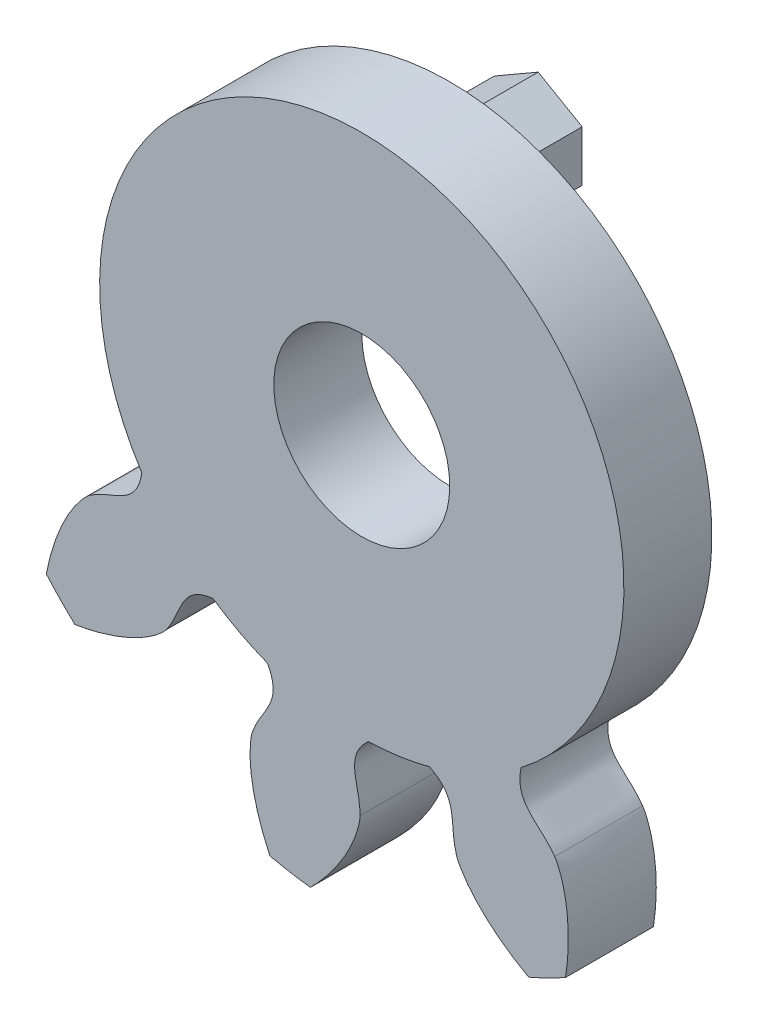
SolidWorks part; units mm, degrees
ref_plane "前视基准面" through (0, 0, 0) normal (0, 0, 1) x (1, 0, 0)
ref_plane "上视基准面" through (0, 0, 0) normal (0, 1, 0) x (1, 0, 0)
ref_plane "右视基准面" through (0, 0, 0) normal (1, 0, 0) x (0, 0, -1)
other "Configuration Table"
sketch "草图1" plane through (0, 0, 0) normal (0, 0, 1) x (1, 0, 0)
  line L0 (0, 0) -> (0.2872, 19.9979) construction
  line L1 (0, 0) -> (4.0944, 23.6482) construction
  line L2 (0, 0) -> (14.9133, 28.2585) construction
  line L3 (4.0944, 23.6482) -> (5.3871, 31.1146) construction
  circle A1 centre (0, 0) radius 15
  circle A2 centre (0, 0) radius 24
  circle A3 centre (0, 0) radius 20
  spline S0 degree 4 poles (0, 18.7939) (0.0002, 18.8091) (0.0018, 18.8518) (0.0091, 18.9324) (0.0267, 19.0633) (0.0577, 19.2291) (0.1075, 19.4417) (0.1785, 19.6895) (0.2696, 19.9587) (0.3823, 20.2475) (0.5069, 20.5317) (0.6419, 20.811) (0.7867, 21.0855) (0.9728, 21.4126) (1.2129, 21.7982) (1.5138, 22.2362) (1.8845, 22.7206) (2.2839, 23.1943) (2.7065, 23.6509) (3.1445, 24.0871) (3.6057, 24.5086) (4.0727, 24.9063) (4.5712, 25.2962) (4.992, 25.6062) (5.402, 25.8856) (5.7469, 26.1147) (6.207, 26.399) (6.5048, 26.5752) (6.9662, 26.8343) (7.1418, 26.9249) (7.2777, 26.9972) knots 0 0 0 0 0 0.005377 0.015084 0.028532 0.04661 0.064855 0.092111 0.119476 0.146842 0.174209 0.201575 0.228941 0.256307 0.307035 0.361767 0.4165 0.471232 0.525964 0.580697 0.635429 0.690161 0.744894 0.799626 0.826992 0.854358 0.909091 0.954545 1 1 1 1 1 construction
  spline S1 degree 4 poles (0, 18.7939) (0.0002, 18.8091) (0.0018, 18.8518) (0.0091, 18.9324) (0.0267, 19.0633) (0.0577, 19.2291) (0.1075, 19.4417) (0.1785, 19.6895) (0.2696, 19.9587) (0.3823, 20.2475) (0.5069, 20.5317) (0.6419, 20.811) (0.7867, 21.0855) (0.9728, 21.4126) (1.2129, 21.7982) (1.5138, 22.2362) (1.8845, 22.7206) (2.2744, 23.1831) (2.5808, 23.5151) (2.7865, 23.7266) (2.8854, 23.8259) knots 0 0 0 0 0 0.005377 0.015084 0.028532 0.04661 0.064855 0.092111 0.119476 0.146842 0.174209 0.201575 0.228941 0.256307 0.307035 0.361767 0.4165 0.471232 0.520763 0.520763 0.520763 0.520763 0.520763
  spline S2 degree 3 poles (0, 18.7939) (-0.0214, 17.2454) (0.9311, 16.2419) (-0.4088, 14.9944) knots 0 0 0 0 1 1 1 1
  spline S3 degree 3 poles (6.3184, 17.6999) (5.818, 16.2344) (4.5835, 15.6095) (5.4261, 13.9842) knots 0 0 0 0 1 1 1 1
  spline S4 degree 4 poles (6.3184, 17.6999) (6.3234, 17.7143) (6.3362, 17.7551) (6.3565, 17.8334) (6.3839, 17.9627) (6.4105, 18.1292) (6.435, 18.3461) (6.4514, 18.6035) (6.4562, 18.8876) (6.4471, 19.1974) (6.4253, 19.507) (6.392, 19.8154) (6.348, 20.1226) (6.2827, 20.4932) (6.1862, 20.9372) (6.0501, 21.4508) (5.8638, 22.0316) (5.652, 22.5983) (5.4751, 23.014) (5.3525, 23.2824) (5.2927, 23.4091) knots 0 0 0 0 0 0.005377 0.015084 0.028532 0.04661 0.064855 0.092111 0.119476 0.146842 0.174209 0.201575 0.228941 0.256307 0.307035 0.361767 0.4165 0.471232 0.520763 0.520763 0.520763 0.520763 0.520763
  spline S5 degree 3 poles (11.0467, 15.2045) (10.1193, 13.9644) (10.3, 12.5926) (8.4828, 12.3711) knots 0 0 0 0 1 1 1 1
  spline S6 degree 4 poles (11.0467, 15.2045) (11.0559, 15.2168) (11.0823, 15.2503) (11.1355, 15.3113) (11.2267, 15.4069) (11.3492, 15.5228) (11.5145, 15.6655) (11.7176, 15.8242) (11.9495, 15.9885) (12.2104, 16.1558) (12.4783, 16.3125) (12.7517, 16.4591) (13.0302, 16.5961) (13.373, 16.7513) (13.794, 16.9222) (14.2948, 17.0997) (14.8794, 17.2736) (15.4667, 17.4186) (15.9097, 17.5071) (16.2005, 17.5574) (16.3389, 17.5795) knots 0 0 0 0 0 0.005377 0.015084 0.028532 0.04661 0.064855 0.092111 0.119476 0.146842 0.174209 0.201575 0.228941 0.256307 0.307035 0.361767 0.4165 0.471232 0.520763 0.520763 0.520763 0.520763 0.520763
  dimension "D1" = 40
  dimension "D2" = 48
  dimension "D3" = 30
  dimension "D4" = 9
  dimension "D5" = 27
sketch "草图2" plane through (0, 0, 0) normal (0, 0, 1) x (1, 0, 0)
  circle A0 centre (0, 0) radius 24 construction
  circle A1 centre (0, 0) radius 15 construction
  arc A2 (5.2927, 23.4091) -> (2.8854, 23.8259) centre (0, 0) ccw
  arc A3 (8.4828, 12.3711) -> (5.4261, 13.9842) centre (0, 0) ccw
  arc A4 (18.0414, 15.8274) -> (16.3389, 17.5795) centre (0, 0) ccw
  arc A5 (14.1342, 5.0224) -> (12.6095, 8.1241) centre (0, 0) ccw
  arc A6 (23.8989, 2.2002) -> (23.5514, 4.6184) centre (0, 0) ccw
  arc A7 (14.3869, -4.2447) -> (14.9765, -0.8392) centre (0, 0) ccw
  arc A8 (20.6279, -12.2675) -> (21.7681, -10.1068) centre (0, 0) ccw
  arc A9 (9.1443, -11.8904) -> (11.623, -9.4819) centre (0, 0) ccw
  arc A10 (9.4777, -22.0494) -> (11.6701, -20.9716) centre (0, 0) ccw
  arc A11 (0.4088, -14.9944) -> (3.8299, -14.5028) centre (0, 0) ccw
  arc A12 (-5.2927, -23.4091) -> (-2.8854, -23.8259) centre (0, 0) ccw
  arc A13 (-8.4828, -12.3711) -> (-5.4261, -13.9842) centre (0, 0) ccw
  arc A14 (-18.0414, -15.8274) -> (-16.3389, -17.5795) centre (0, 0) ccw
  arc A15 (-14.1342, -5.0224) -> (-12.6095, -8.1241) centre (0, 0) ccw
  arc A16 (-23.8989, -2.2002) -> (-23.5514, -4.6184) centre (0, 0) ccw
  arc A17 (-14.3869, 4.2447) -> (-14.9765, 0.8392) centre (0, 0) ccw
  arc A18 (-20.6279, 12.2675) -> (-21.7681, 10.1068) centre (0, 0) ccw
  arc A19 (-9.1443, 11.8904) -> (-11.623, 9.4819) centre (0, 0) ccw
  arc A20 (-9.4777, 22.0494) -> (-11.6701, 20.9716) centre (0, 0) ccw
  arc A21 (-0.4088, 14.9944) -> (-3.8299, 14.5028) centre (0, 0) ccw
  spline S0 degree 3 poles (11.0467, 15.2045) (10.1193, 13.9644) (10.3, 12.5926) (8.4828, 12.3711) knots 0 0 0 0 1 1 1 1
  spline S1 degree 4 poles (11.0467, 15.2045) (11.0559, 15.2168) (11.0823, 15.2503) (11.1355, 15.3113) (11.2267, 15.4069) (11.3492, 15.5228) (11.5145, 15.6655) (11.7176, 15.8242) (11.9495, 15.9885) (12.2104, 16.1558) (12.4783, 16.3125) (12.7517, 16.4591) (13.0302, 16.5961) (13.373, 16.7513) (13.794, 16.9222) (14.2948, 17.0997) (14.8794, 17.2736) (15.4667, 17.4186) (15.9097, 17.5071) (16.2005, 17.5574) (16.3389, 17.5795) knots 0 0 0 0 0 0.005377 0.015084 0.028532 0.04661 0.064855 0.092111 0.119476 0.146842 0.174209 0.201575 0.228941 0.256307 0.307035 0.361767 0.4165 0.471232 0.520763 0.520763 0.520763 0.520763 0.520763
  spline S2 degree 3 poles (-1612.2775, 1191.9334) (1670.8428, -1086.4316) (-1683.6777, 1084.3707) (1696.3854, -1053.879) knots -8.087101 -8.087101 -8.087101 -8.087101 8.731243 8.731243 8.731243 8.731243 only from (6.3184, 17.6999) to (5.4261, 13.9842) construction
  spline S3 degree 4 poles (-1871.5282, 705.077) (-26.1051, 25.3219) (4.9134, 15.562) (6.1018, 16.6335) (6.3839, 17.9627) (6.4105, 18.1292) (6.435, 18.3461) (6.4514, 18.6035) (6.4562, 18.8876) (6.4471, 19.1974) (6.4253, 19.507) (6.392, 19.8154) (6.348, 20.1226) (6.2827, 20.4932) (6.1862, 20.9372) (6.0501, 21.4508) (5.8638, 22.0316) (3.5005, 28.3573) (-2.9853, 33.2696) (5.6158, 19.648) (-1289.4737, 1547.6734) knots -0.432729 -0.432729 -0.432729 -0.432729 -0.432729 0.005377 0.015084 0.028532 0.04661 0.064855 0.092111 0.119476 0.146842 0.174209 0.201575 0.228941 0.256307 0.307035 0.361767 0.4165 0.471232 2.692745 2.692745 2.692745 2.692745 2.692745 only from (6.3184, 17.6999) to (5.2927, 23.4091) construction
  spline S4 degree 3 poles (1919.1538, 580.5106) (-1938.8407, -461.4604) (1950.2357, 455.2045) (-1951.9525, -422.2153) knots -8.087101 -8.087101 -8.087101 -8.087101 8.731243 8.731243 8.731243 8.731243 only from (0, 18.7939) to (-0.4088, 14.9944) construction
  spline S5 degree 4 poles (1999.6344, 34.8341) (33.0987, 15.0715) (0.6044, 16.308) (-0.1545, 17.7168) (0.0267, 19.0633) (0.0577, 19.2291) (0.1075, 19.4417) (0.1785, 19.6895) (0.2696, 19.9587) (0.3823, 20.2475) (0.5069, 20.5317) (0.6419, 20.811) (0.7867, 21.0855) (0.9728, 21.4126) (1.2129, 21.7982) (1.5138, 22.2362) (1.8845, 22.7206) (6.2369, 27.8835) (13.9967, 30.3294) (1.3166, 20.3923) (1734.7385, 1024.0692) knots -0.432729 -0.432729 -0.432729 -0.432729 -0.432729 0.005377 0.015084 0.028532 0.04661 0.064855 0.092111 0.119476 0.146842 0.174209 0.201575 0.228941 0.256307 0.307035 0.361767 0.4165 0.471232 2.692745 2.692745 2.692745 2.692745 2.692745 only from (0, 18.7939) to (2.8854, 23.8259) construction
  spline S6 degree 4 poles (15.5155, 10.6056) (15.5279, 10.6144) (15.5623, 10.6399) (15.6247, 10.6913) (15.7229, 10.7797) (15.8422, 10.8988) (15.9896, 11.0599) (16.1541, 11.2585) (16.325, 11.4855) (16.4998, 11.7415) (16.6641, 12.0048) (16.8184, 12.2739) (16.9634, 12.5483) (17.1284, 12.8865) (17.3113, 13.3024) (17.5031, 13.7979) (17.6937, 14.3773) (17.8555, 14.9602) (17.9567, 15.4005) (18.0153, 15.6897) (18.0414, 15.8274) knots 0 0 0 0 0 0.005377 0.015084 0.028532 0.04661 0.064855 0.092111 0.119476 0.146842 0.174209 0.201575 0.228941 0.256307 0.307035 0.361767 0.4165 0.471232 0.520763 0.520763 0.520763 0.520763 0.520763
  spline S7 degree 3 poles (15.5155, 10.6056) (14.2492, 9.7142) (12.8832, 9.9342) (12.6095, 8.1241) knots 0 0 0 0 1 1 1 1
  spline S8 degree 3 poles (6.3184, 17.6999) (5.818, 16.2344) (4.5835, 15.6095) (5.4261, 13.9842) knots 0 0 0 0 1 1 1 1
  spline S9 degree 4 poles (6.3184, 17.6999) (6.3234, 17.7143) (6.3362, 17.7551) (6.3565, 17.8334) (6.3839, 17.9627) (6.4105, 18.1292) (6.435, 18.3461) (6.4514, 18.6035) (6.4562, 18.8876) (6.4471, 19.1974) (6.4253, 19.507) (6.392, 19.8154) (6.348, 20.1226) (6.2827, 20.4932) (6.1862, 20.9372) (6.0501, 21.4508) (5.8638, 22.0316) (5.652, 22.5983) (5.4751, 23.014) (5.3525, 23.2824) (5.2927, 23.4091) knots 0 0 0 0 0 0.005377 0.015084 0.028532 0.04661 0.064855 0.092111 0.119476 0.146842 0.174209 0.201575 0.228941 0.256307 0.307035 0.361767 0.4165 0.471232 0.520763 0.520763 0.520763 0.520763 0.520763
  spline S10 degree 3 poles (0, 18.7939) (-0.0214, 17.2454) (0.9311, 16.2419) (-0.4088, 14.9944) knots 0 0 0 0 1 1 1 1
  spline S11 degree 4 poles (0, 18.7939) (0.0002, 18.8091) (0.0018, 18.8518) (0.0091, 18.9324) (0.0267, 19.0633) (0.0577, 19.2291) (0.1075, 19.4417) (0.1785, 19.6895) (0.2696, 19.9587) (0.3823, 20.2475) (0.5069, 20.5317) (0.6419, 20.811) (0.7867, 21.0855) (0.9728, 21.4126) (1.2129, 21.7982) (1.5138, 22.2362) (1.8845, 22.7206) (2.2744, 23.1831) (2.5808, 23.5151) (2.7865, 23.7266) (2.8854, 23.8259) knots 0 0 0 0 0 0.005377 0.015084 0.028532 0.04661 0.064855 0.092111 0.119476 0.146842 0.174209 0.201575 0.228941 0.256307 0.307035 0.361767 0.4165 0.471232 0.520763 0.520763 0.520763 0.520763 0.520763
  spline S12 degree 3 poles (17.874, 5.8076) (16.3947, 5.3494) (15.7347, 4.1335) (14.1342, 5.0224) knots 0 0 0 0 1 1 1 1
  spline S13 degree 4 poles (17.874, 5.8076) (17.8886, 5.8121) (17.9297, 5.8238) (18.0086, 5.8418) (18.1385, 5.8655) (18.3058, 5.8873) (18.5234, 5.9056) (18.781, 5.9146) (19.0652, 5.9112) (19.3746, 5.8932) (19.6834, 5.8626) (19.9908, 5.8204) (20.2966, 5.7676) (20.6652, 5.6917) (21.1062, 5.5825) (21.6157, 5.4317) (22.1909, 5.2288) (22.7513, 5.0009) (23.1617, 4.8121) (23.4264, 4.6818) (23.5514, 4.6184) knots 0 0 0 0 0 0.005377 0.015084 0.028532 0.04661 0.064855 0.092111 0.119476 0.146842 0.174209 0.201575 0.228941 0.256307 0.307035 0.361767 0.4165 0.471232 0.520763 0.520763 0.520763 0.520763 0.520763
  spline S14 degree 4 poles (18.7861, -0.5396) (18.8013, -0.5398) (18.8441, -0.5394) (18.9248, -0.5345) (19.0562, -0.5207) (19.2228, -0.4945) (19.4368, -0.4508) (19.6865, -0.3869) (19.9582, -0.3036) (20.2501, -0.1992) (20.5378, -0.0829) (20.8208, 0.0441) (21.0993, 0.1809) (21.4317, 0.3576) (21.8241, 0.5865) (22.2705, 0.8747) (22.7653, 1.2314) (23.2388, 1.6078) (23.5795, 1.9046) (23.7969, 2.1041) (23.8989, 2.2002) knots 0 0 0 0 0 0.005377 0.015084 0.028532 0.04661 0.064855 0.092111 0.119476 0.146842 0.174209 0.201575 0.228941 0.256307 0.307035 0.361767 0.4165 0.471232 0.520763 0.520763 0.520763 0.520763 0.520763
  spline S15 degree 3 poles (18.7861, -0.5396) (17.2377, -0.5165) (16.2619, 0.4644) (14.9765, -0.8392) knots 0 0 0 0 1 1 1 1
  spline S16 degree 3 poles (17.874, -5.8076) (16.4079, -5.3088) (15.1592, -5.9046) (14.3869, -4.2447) knots 0 0 0 0 1 1 1 1
  spline S17 degree 4 poles (17.874, -5.8076) (17.8884, -5.8125) (17.9286, -5.8273) (18.003, -5.859) (18.1221, -5.9163) (18.2701, -5.997) (18.4569, -6.11) (18.6707, -6.2542) (18.8985, -6.424) (19.1384, -6.6204) (19.3701, -6.8267) (19.594, -7.0415) (19.8104, -7.2639) (20.064, -7.542) (20.3566, -7.8896) (20.6801, -8.3111) (21.0262, -8.8133) (21.3456, -9.3271) (21.5667, -9.7211) (21.7043, -9.982) (21.7681, -10.1068) knots 0 0 0 0 0 0.005377 0.015084 0.028532 0.04661 0.064855 0.092111 0.119476 0.146842 0.174209 0.201575 0.228941 0.256307 0.307035 0.361767 0.4165 0.471232 0.520763 0.520763 0.520763 0.520763 0.520763
  spline S18 degree 4 poles (14.8811, -11.4788) (14.8933, -11.4879) (14.9281, -11.5127) (14.9963, -11.5562) (15.1108, -11.6222) (15.2609, -11.6989) (15.4597, -11.7893) (15.6993, -11.8844) (15.9681, -11.9768) (16.2656, -12.0639) (16.5667, -12.1388) (16.8703, -12.2025) (17.1761, -12.2555) (17.5488, -12.3079) (18.0008, -12.3534) (18.5314, -12.3826) (19.1413, -12.3849) (19.7457, -12.3587) (20.1957, -12.3188) (20.4888, -12.2852) (20.6279, -12.2675) knots 0 0 0 0 0 0.005377 0.015084 0.028532 0.04661 0.064855 0.092111 0.119476 0.146842 0.174209 0.201575 0.228941 0.256307 0.307035 0.361767 0.4165 0.471232 0.520763 0.520763 0.520763 0.520763 0.520763
  spline S19 degree 3 poles (14.8811, -11.4788) (13.642, -10.5499) (13.4291, -9.1828) (11.623, -9.4819) knots 0 0 0 0 1 1 1 1
  spline S20 degree 3 poles (11.0467, -15.2045) (10.1539, -13.9393) (8.7934, -13.6872) (9.1443, -11.8904) knots 0 0 0 0 1 1 1 1
  spline S21 degree 4 poles (11.0467, -15.2045) (11.0555, -15.217) (11.0793, -15.2525) (11.1209, -15.322) (11.1836, -15.4382) (11.2559, -15.5906) (11.3406, -15.7918) (11.4288, -16.0341) (11.5133, -16.3054) (11.5919, -16.6052) (11.6581, -16.9084) (11.713, -17.2137) (11.7573, -17.5209) (11.799, -17.8949) (11.8314, -18.3481) (11.8454, -18.8793) (11.8302, -19.489) (11.7866, -20.0924) (11.7339, -20.5411) (11.6919, -20.8331) (11.6701, -20.9716) knots 0 0 0 0 0 0.005377 0.015084 0.028532 0.04661 0.064855 0.092111 0.119476 0.146842 0.174209 0.201575 0.228941 0.256307 0.307035 0.361767 0.4165 0.471232 0.520763 0.520763 0.520763 0.520763 0.520763
  spline S22 degree 4 poles (5.292, -18.0334) (5.2965, -18.048) (5.3101, -18.0885) (5.3397, -18.1638) (5.3935, -18.2845) (5.4699, -18.4348) (5.5776, -18.6248) (5.7155, -18.8426) (5.8787, -19.0752) (6.0681, -19.3206) (6.2677, -19.5582) (6.476, -19.7881) (6.6921, -20.0108) (6.9629, -20.2722) (7.3018, -20.5747) (7.7139, -20.9102) (8.206, -21.2706) (8.7104, -21.6046) (9.0978, -21.8369) (9.3547, -21.982) (9.4777, -22.0494) knots 0 0 0 0 0 0.005377 0.015084 0.028532 0.04661 0.064855 0.092111 0.119476 0.146842 0.174209 0.201575 0.228941 0.256307 0.307035 0.361767 0.4165 0.471232 0.520763 0.520763 0.520763 0.520763 0.520763
  spline S23 degree 3 poles (5.292, -18.0334) (4.8355, -16.5536) (5.4669, -15.3225) (3.8299, -14.5028) knots 0 0 0 0 1 1 1 1
  spline S24 degree 3 poles (0, -18.7939) (0.0214, -17.2454) (-0.9311, -16.2419) (0.4088, -14.9944) knots 0 0 0 0 1 1 1 1
  spline S25 degree 4 poles (0, -18.7939) (-0.0002, -18.8091) (-0.0018, -18.8518) (-0.0091, -18.9324) (-0.0267, -19.0633) (-0.0577, -19.2291) (-0.1075, -19.4417) (-0.1785, -19.6895) (-0.2696, -19.9587) (-0.3823, -20.2475) (-0.5069, -20.5317) (-0.6419, -20.811) (-0.7867, -21.0855) (-0.9728, -21.4126) (-1.2129, -21.7982) (-1.5138, -22.2362) (-1.8845, -22.7206) (-2.2744, -23.1831) (-2.5808, -23.5151) (-2.7865, -23.7266) (-2.8854, -23.8259) knots 0 0 0 0 0 0.005377 0.015084 0.028532 0.04661 0.064855 0.092111 0.119476 0.146842 0.174209 0.201575 0.228941 0.256307 0.307035 0.361767 0.4165 0.471232 0.520763 0.520763 0.520763 0.520763 0.520763
  spline S26 degree 4 poles (-6.3184, -17.6999) (-6.3234, -17.7143) (-6.3362, -17.7551) (-6.3565, -17.8334) (-6.3839, -17.9627) (-6.4105, -18.1292) (-6.435, -18.3461) (-6.4514, -18.6035) (-6.4562, -18.8876) (-6.4471, -19.1974) (-6.4253, -19.507) (-6.392, -19.8154) (-6.348, -20.1226) (-6.2827, -20.4932) (-6.1862, -20.9372) (-6.0501, -21.4508) (-5.8638, -22.0316) (-5.652, -22.5983) (-5.4751, -23.014) (-5.3525, -23.2824) (-5.2927, -23.4091) knots 0 0 0 0 0 0.005377 0.015084 0.028532 0.04661 0.064855 0.092111 0.119476 0.146842 0.174209 0.201575 0.228941 0.256307 0.307035 0.361767 0.4165 0.471232 0.520763 0.520763 0.520763 0.520763 0.520763
  spline S27 degree 3 poles (-6.3184, -17.6999) (-5.818, -16.2344) (-4.5835, -15.6095) (-5.4261, -13.9842) knots 0 0 0 0 1 1 1 1
  spline S28 degree 3 poles (-11.0467, -15.2045) (-10.1193, -13.9644) (-10.3, -12.5926) (-8.4828, -12.3711) knots 0 0 0 0 1 1 1 1
  spline S29 degree 4 poles (-11.0467, -15.2045) (-11.0559, -15.2168) (-11.0823, -15.2503) (-11.1355, -15.3113) (-11.2267, -15.4069) (-11.3492, -15.5228) (-11.5145, -15.6655) (-11.7176, -15.8242) (-11.9495, -15.9885) (-12.2104, -16.1558) (-12.4783, -16.3125) (-12.7517, -16.4591) (-13.0302, -16.5961) (-13.373, -16.7513) (-13.794, -16.9222) (-14.2948, -17.0997) (-14.8794, -17.2736) (-15.4667, -17.4186) (-15.9097, -17.5071) (-16.2005, -17.5574) (-16.3389, -17.5795) knots 0 0 0 0 0 0.005377 0.015084 0.028532 0.04661 0.064855 0.092111 0.119476 0.146842 0.174209 0.201575 0.228941 0.256307 0.307035 0.361767 0.4165 0.471232 0.520763 0.520763 0.520763 0.520763 0.520763
  spline S30 degree 4 poles (-15.5155, -10.6056) (-15.5279, -10.6144) (-15.5623, -10.6399) (-15.6247, -10.6913) (-15.7229, -10.7797) (-15.8422, -10.8988) (-15.9896, -11.0599) (-16.1541, -11.2585) (-16.325, -11.4855) (-16.4998, -11.7415) (-16.6641, -12.0048) (-16.8184, -12.2739) (-16.9634, -12.5483) (-17.1284, -12.8865) (-17.3113, -13.3024) (-17.5031, -13.7979) (-17.6937, -14.3773) (-17.8555, -14.9602) (-17.9567, -15.4005) (-18.0153, -15.6897) (-18.0414, -15.8274) knots 0 0 0 0 0 0.005377 0.015084 0.028532 0.04661 0.064855 0.092111 0.119476 0.146842 0.174209 0.201575 0.228941 0.256307 0.307035 0.361767 0.4165 0.471232 0.520763 0.520763 0.520763 0.520763 0.520763
  spline S31 degree 3 poles (-15.5155, -10.6056) (-14.2492, -9.7142) (-12.8832, -9.9342) (-12.6095, -8.1241) knots 0 0 0 0 1 1 1 1
  spline S32 degree 3 poles (-17.874, -5.8076) (-16.3947, -5.3494) (-15.7347, -4.1335) (-14.1342, -5.0224) knots 0 0 0 0 1 1 1 1
  spline S33 degree 4 poles (-17.874, -5.8076) (-17.8886, -5.8121) (-17.9297, -5.8238) (-18.0086, -5.8418) (-18.1385, -5.8655) (-18.3058, -5.8873) (-18.5234, -5.9056) (-18.781, -5.9146) (-19.0652, -5.9112) (-19.3746, -5.8932) (-19.6834, -5.8626) (-19.9908, -5.8204) (-20.2966, -5.7676) (-20.6652, -5.6917) (-21.1062, -5.5825) (-21.6157, -5.4317) (-22.1909, -5.2288) (-22.7513, -5.0009) (-23.1617, -4.8121) (-23.4264, -4.6818) (-23.5514, -4.6184) knots 0 0 0 0 0 0.005377 0.015084 0.028532 0.04661 0.064855 0.092111 0.119476 0.146842 0.174209 0.201575 0.228941 0.256307 0.307035 0.361767 0.4165 0.471232 0.520763 0.520763 0.520763 0.520763 0.520763
  spline S34 degree 4 poles (-18.7861, 0.5396) (-18.8013, 0.5398) (-18.8441, 0.5394) (-18.9248, 0.5345) (-19.0562, 0.5207) (-19.2228, 0.4945) (-19.4368, 0.4508) (-19.6865, 0.3869) (-19.9582, 0.3036) (-20.2501, 0.1992) (-20.5378, 0.0829) (-20.8208, -0.0441) (-21.0993, -0.1809) (-21.4317, -0.3576) (-21.8241, -0.5865) (-22.2705, -0.8747) (-22.7653, -1.2314) (-23.2388, -1.6078) (-23.5795, -1.9046) (-23.7969, -2.1041) (-23.8989, -2.2002) knots 0 0 0 0 0 0.005377 0.015084 0.028532 0.04661 0.064855 0.092111 0.119476 0.146842 0.174209 0.201575 0.228941 0.256307 0.307035 0.361767 0.4165 0.471232 0.520763 0.520763 0.520763 0.520763 0.520763
  spline S35 degree 3 poles (-18.7861, 0.5396) (-17.2377, 0.5165) (-16.2619, -0.4644) (-14.9765, 0.8392) knots 0 0 0 0 1 1 1 1
  spline S36 degree 3 poles (-17.874, 5.8076) (-16.4079, 5.3088) (-15.1592, 5.9046) (-14.3869, 4.2447) knots 0 0 0 0 1 1 1 1
  spline S37 degree 4 poles (-17.874, 5.8076) (-17.8884, 5.8125) (-17.9286, 5.8273) (-18.003, 5.859) (-18.1221, 5.9163) (-18.2701, 5.997) (-18.4569, 6.11) (-18.6707, 6.2542) (-18.8985, 6.424) (-19.1384, 6.6204) (-19.3701, 6.8267) (-19.594, 7.0415) (-19.8104, 7.2639) (-20.064, 7.542) (-20.3566, 7.8896) (-20.6801, 8.3111) (-21.0262, 8.8133) (-21.3456, 9.3271) (-21.5667, 9.7211) (-21.7043, 9.982) (-21.7681, 10.1068) knots 0 0 0 0 0 0.005377 0.015084 0.028532 0.04661 0.064855 0.092111 0.119476 0.146842 0.174209 0.201575 0.228941 0.256307 0.307035 0.361767 0.4165 0.471232 0.520763 0.520763 0.520763 0.520763 0.520763
  spline S38 degree 4 poles (-14.8811, 11.4788) (-14.8933, 11.4879) (-14.9281, 11.5127) (-14.9963, 11.5562) (-15.1108, 11.6222) (-15.2609, 11.6989) (-15.4597, 11.7893) (-15.6993, 11.8844) (-15.9681, 11.9768) (-16.2656, 12.0639) (-16.5667, 12.1388) (-16.8703, 12.2025) (-17.1761, 12.2555) (-17.5488, 12.3079) (-18.0008, 12.3534) (-18.5314, 12.3826) (-19.1413, 12.3849) (-19.7457, 12.3587) (-20.1957, 12.3188) (-20.4888, 12.2852) (-20.6279, 12.2675) knots 0 0 0 0 0 0.005377 0.015084 0.028532 0.04661 0.064855 0.092111 0.119476 0.146842 0.174209 0.201575 0.228941 0.256307 0.307035 0.361767 0.4165 0.471232 0.520763 0.520763 0.520763 0.520763 0.520763
  spline S39 degree 3 poles (-14.8811, 11.4788) (-13.642, 10.5499) (-13.4291, 9.1828) (-11.623, 9.4819) knots 0 0 0 0 1 1 1 1
  spline S40 degree 3 poles (-11.0467, 15.2045) (-10.1539, 13.9393) (-8.7934, 13.6872) (-9.1443, 11.8904) knots 0 0 0 0 1 1 1 1
  spline S41 degree 4 poles (-11.0467, 15.2045) (-11.0555, 15.217) (-11.0793, 15.2525) (-11.1209, 15.322) (-11.1836, 15.4382) (-11.2559, 15.5906) (-11.3406, 15.7918) (-11.4288, 16.0341) (-11.5133, 16.3054) (-11.5919, 16.6052) (-11.6581, 16.9084) (-11.713, 17.2137) (-11.7573, 17.5209) (-11.799, 17.8949) (-11.8314, 18.3481) (-11.8454, 18.8793) (-11.8302, 19.489) (-11.7866, 20.0924) (-11.7339, 20.5411) (-11.6919, 20.8331) (-11.6701, 20.9716) knots 0 0 0 0 0 0.005377 0.015084 0.028532 0.04661 0.064855 0.092111 0.119476 0.146842 0.174209 0.201575 0.228941 0.256307 0.307035 0.361767 0.4165 0.471232 0.520763 0.520763 0.520763 0.520763 0.520763
  spline S42 degree 4 poles (-5.292, 18.0334) (-5.2965, 18.048) (-5.3101, 18.0885) (-5.3397, 18.1638) (-5.3935, 18.2845) (-5.4699, 18.4348) (-5.5776, 18.6248) (-5.7155, 18.8426) (-5.8787, 19.0752) (-6.0681, 19.3206) (-6.2677, 19.5582) (-6.476, 19.7881) (-6.6921, 20.0108) (-6.9629, 20.2722) (-7.3018, 20.5747) (-7.7139, 20.9102) (-8.206, 21.2706) (-8.7104, 21.6046) (-9.0978, 21.8369) (-9.3547, 21.982) (-9.4777, 22.0494) knots 0 0 0 0 0 0.005377 0.015084 0.028532 0.04661 0.064855 0.092111 0.119476 0.146842 0.174209 0.201575 0.228941 0.256307 0.307035 0.361767 0.4165 0.471232 0.520763 0.520763 0.520763 0.520763 0.520763
  spline S43 degree 3 poles (-5.292, 18.0334) (-4.8355, 16.5536) (-5.4669, 15.3225) (-3.8299, 14.5028) knots 0 0 0 0 1 1 1 1
  point P76 (0, 0)
  dimension "D1" = 10
sketch "草图4" plane through (0, 0, 0) normal (0, 0, 1) x (1, 0, 0)
  arc A20 (20.5668, -12.1744) -> (21.6568, -10.109) centre (0, 0) ccw
  arc A21 (20.5668, -12.1744) -> (21.6568, -10.109) centre (0, 0) ccw
  arc A22 (14.2802, -4.2526) -> (14.8787, -0.7959) centre (0, 0) ccw
  arc A23 (14.2802, -4.2526) -> (14.8787, -0.7959) centre (0, 0) ccw
  arc A24 (23.7948, 2.2396) -> (23.4627, 4.5512) centre (0, 0) ccw
  arc A25 (23.7948, 2.2396) -> (23.4627, 4.5512) centre (0, 0) ccw
  arc A26 (14.0526, 4.9533) -> (12.505, 8.1016) centre (0, 0) ccw
  arc A27 (14.0526, 4.9533) -> (12.505, 8.1016) centre (0, 0) ccw
  arc A28 (17.934, 15.7981) -> (16.3065, 17.473) centre (0, 0) ccw
  arc A29 (17.934, 15.7981) -> (16.3065, 17.473) centre (0, 0) ccw
  arc A30 (8.4573, 12.2672) -> (5.3547, 13.9046) centre (0, 0) ccw
  arc A31 (8.4573, 12.2672) -> (5.3547, 13.9046) centre (0, 0) ccw
  arc A32 (5.223, 23.3223) -> (2.9219, 23.7207) centre (0, 0) ccw
  arc A33 (5.223, 23.3223) -> (2.9219, 23.7207) centre (0, 0) ccw
  arc A34 (-0.3684, 14.8954) -> (-3.8408, 14.3965) centre (0, 0) ccw
  arc A35 (-0.3684, 14.8954) -> (-3.8408, 14.3965) centre (0, 0) ccw
  arc A36 (-9.483, 21.9382) -> (-11.5788, 20.9079) centre (0, 0) ccw
  arc A37 (-9.483, 21.9382) -> (-11.5788, 20.9079) centre (0, 0) ccw
  arc A38 (-9.0534, 11.8341) -> (-11.5693, 9.3894) centre (0, 0) ccw
  arc A39 (-9.0534, 11.8341) -> (-11.5693, 9.3894) centre (0, 0) ccw
  arc A40 (9.0534, -11.8341) -> (11.5693, -9.3894) centre (0, 0) ccw
  arc A41 (-20.5668, 12.1744) -> (-21.6568, 10.109) centre (0, 0) ccw
  arc A42 (-20.5668, 12.1744) -> (-21.6568, 10.109) centre (0, 0) ccw
  arc A43 (-14.2802, 4.2526) -> (-14.8787, 0.7959) centre (0, 0) ccw
  arc A44 (-14.2802, 4.2526) -> (-14.8787, 0.7959) centre (0, 0) ccw
  arc A45 (-23.7948, -2.2396) -> (-23.4627, -4.5512) centre (0, 0) ccw
  arc A46 (-23.7948, -2.2396) -> (-23.4627, -4.5512) centre (0, 0) ccw
  arc A47 (-14.0526, -4.9533) -> (-12.505, -8.1016) centre (0, 0) ccw
  arc A48 (-14.0526, -4.9533) -> (-12.505, -8.1016) centre (0, 0) ccw
  arc A49 (-17.934, -15.7981) -> (-16.3065, -17.473) centre (0, 0) ccw
  arc A50 (-17.934, -15.7981) -> (-16.3065, -17.473) centre (0, 0) ccw
  arc A51 (-8.4573, -12.2672) -> (-5.3547, -13.9046) centre (0, 0) ccw
  arc A52 (-8.4573, -12.2672) -> (-5.3547, -13.9046) centre (0, 0) ccw
  arc A53 (-5.223, -23.3223) -> (-2.9219, -23.7207) centre (0, 0) ccw
  arc A54 (-5.223, -23.3223) -> (-2.9219, -23.7207) centre (0, 0) ccw
  arc A55 (0.3684, -14.8954) -> (3.8408, -14.3965) centre (0, 0) ccw
  arc A56 (0.3684, -14.8954) -> (3.8408, -14.3965) centre (0, 0) ccw
  arc A57 (9.483, -21.9382) -> (11.5788, -20.9079) centre (0, 0) ccw
  arc A58 (9.483, -21.9382) -> (11.5788, -20.9079) centre (0, 0) ccw
  arc A60 (9.0534, -11.8341) -> (11.5693, -9.3894) centre (0, 0) ccw
  spline S40 degree 3 poles (-692.041, -726.443) (13.4993, -40.0823) (17.8818, -21.5749) (10.0164, -14.2565) (9.7491, -14.0335) (9.4055, -13.646) (9.2999, -13.5052) (9.1325, -13.2022) (9.0706, -13.0399) (8.9957, -12.6988) (8.9833, -12.5263) (9.2517, -4.3222) (51.2123, 2.3962) (-983.6174, -132.4669) knots -7.256804 -7.256804 -7.256804 -7.256804 0.25 0.25 0.5 0.5 0.625 0.625 0.75 0.75 0.875 0.875 6.648463 6.648463 6.648463 6.648463 only from (10.965, -15.2622) to (9.0534, -11.8341)
  spline S41 degree 3 poles (10.965, -15.2622) (10.7636, -14.9767) (10.5234, -14.7282) (10.0164, -14.2565) (9.7491, -14.0335) (9.4055, -13.646) (9.2999, -13.5052) (9.1325, -13.2022) (9.0706, -13.0399) (8.9957, -12.6988) (8.9833, -12.5263) (8.9947, -12.1786) (9.0199, -12.0053) (9.0534, -11.8341) knots 0 0 0 0 0.25 0.25 0.5 0.5 0.625 0.625 0.75 0.75 0.875 0.875 1 1 1 1
  spline S42 degree 3 poles (-52.7345, 988.5371) (-2.4626, -51.8011) (3.9531, -9.3869) (12.2572, -9.339) (12.4328, -9.3564) (12.7676, -9.4392) (12.9299, -9.5055) (13.2293, -9.6814) (13.3649, -9.7888) (13.7466, -10.1461) (13.9616, -10.42) (21.1064, -18.5566) (39.7447, -14.1778) (727.7532, 689.9541) knots -5.769385 -5.769385 -5.769385 -5.769385 0.125 0.125 0.25 0.25 0.375 0.375 0.5 0.5 0.75 0.75 8.292557 8.292557 8.292557 8.292557 only from (11.5693, -9.3894) to (14.9411, -11.3987)
  spline S43 degree 3 poles (11.5693, -9.3894) (11.7406, -9.361) (11.9123, -9.341) (12.2572, -9.339) (12.4328, -9.3564) (12.7676, -9.4392) (12.9299, -9.5055) (13.2293, -9.6814) (13.3649, -9.7888) (13.7466, -10.1461) (13.9616, -10.42) (14.4201, -10.9421) (14.6622, -11.1897) (14.9411, -11.3987) knots 0 0 0 0 0.125 0.125 0.25 0.25 0.375 0.375 0.5 0.5 0.75 0.75 1 1 1 1
  spline S44 degree 3 poles (437.5128, 894.9224) (10.6175, -4.9144) (12.1037, -9.7777) (15.1473, -11.5271) (15.2006, -11.5554) (15.3626, -11.6364) (15.473, -11.6852) (15.8096, -11.8207) (16.041, -11.896) (16.7365, -12.0865) (17.2076, -12.1686) (18.1603, -12.2698) (18.644, -12.2881) (52.9773, -11.648) (79.7589, 123.6032) (172.6817, -1000.535) knots -1.750143 -1.750143 -1.750143 -1.750143 0.03125 0.03125 0.0625 0.0625 0.125 0.125 0.25 0.25 0.5 0.5 0.75 0.75 18.31793 18.31793 18.31793 18.31793 only from (14.9411, -11.3987) to (20.5668, -12.1744)
  spline S45 degree 3 poles (14.9411, -11.3987) (14.9903, -11.4356) (15.0423, -11.4668) (15.1473, -11.5271) (15.2006, -11.5554) (15.3626, -11.6364) (15.473, -11.6852) (15.8096, -11.8207) (16.041, -11.896) (16.7365, -12.0865) (17.2076, -12.1686) (18.1603, -12.2698) (18.644, -12.2881) (19.6075, -12.2701) (20.0878, -12.2339) (20.5668, -12.1744) knots 0 0 0 0 0.03125 0.03125 0.0625 0.0625 0.125 0.125 0.25 0.25 0.5 0.5 0.75 0.75 1 1 1 1
  spline S46 degree 3 poles (393.0194, 918.3788) (-41.148, -135.3815) (39.7753, -30.8492) (19.7555, -7.3378) (19.4182, -6.9921) (18.8689, -6.5265) (18.6776, -6.3793) (18.3764, -6.1784) (18.274, -6.1151) (18.1163, -6.0274) (18.063, -5.9995) (14.8975, -4.4737) (10.067, -6.0685) (-476.634, -874.9598) knots -15.286721 -15.286721 -15.286721 -15.286721 0.5 0.5 0.75 0.75 0.875 0.875 0.9375 0.9375 0.96875 0.96875 2.760236 2.760236 2.760236 2.760236 only from (21.6568, -10.109) to (17.8418, -5.9023)
  spline S47 degree 3 poles (21.6568, -10.109) (21.215, -9.252) (20.6917, -8.4374) (19.7555, -7.3378) (19.4182, -6.9921) (18.8689, -6.5265) (18.6776, -6.3793) (18.3764, -6.1784) (18.274, -6.1151) (18.1163, -6.0274) (18.063, -5.9995) (17.9545, -5.9472) (17.8997, -5.922) (17.8418, -5.9023) knots 0 0 0 0 0.5 0.5 0.75 0.75 0.875 0.875 0.9375 0.9375 0.96875 0.96875 1 1 1 1
  spline S48 degree 3 poles (-132.8805, -994.4763) (34.4809, -24.4926) (27.1481, -6.9438) (16.4832, -5.6462) (16.1358, -5.6229) (15.6301, -5.5114) (15.462, -5.4596) (15.1484, -5.3129) (15.0029, -5.218) (14.7418, -4.986) (14.6304, -4.8537) (10.0253, 1.9413) (40.0232, 32.0404) (-717.9011, -685.3238) knots -7.256804 -7.256804 -7.256804 -7.256804 0.25 0.25 0.5 0.5 0.625 0.625 0.75 0.75 0.875 0.875 6.648463 6.648463 6.648463 6.648463 only from (17.8418, -5.9023) to (14.2802, -4.2526)
  spline S49 degree 3 poles (17.8418, -5.9023) (17.511, -5.7898) (17.1706, -5.7299) (16.4832, -5.6462) (16.1358, -5.6229) (15.6301, -5.5114) (15.462, -5.4596) (15.1484, -5.3129) (15.0029, -5.218) (14.7418, -4.986) (14.6304, -4.8537) (14.4353, -4.5657) (14.3538, -4.4107) (14.2802, -4.2526) knots 0 0 0 0 0.25 0.25 0.5 0.5 0.625 0.625 0.75 0.75 0.875 0.875 1 1 1 1
  spline S50 degree 3 poles (-623.7106, 768.7468) (28.4557, -43.3555) (8.7156, -5.2706) (15.4056, -0.3508) (15.5579, -0.2617) (15.8774, -0.1318) (16.0477, -0.0901) (16.3933, -0.0564) (16.5662, -0.0636) (17.085, -0.1284) (17.4199, -0.2235) (27.9827, -2.6065) (40.4877, 11.8912) (183.2199, 985.9472) knots -5.769385 -5.769385 -5.769385 -5.769385 0.125 0.125 0.25 0.25 0.375 0.375 0.5 0.5 0.75 0.75 8.292557 8.292557 8.292557 8.292557 only from (14.8787, -0.7959) to (18.7876, -0.4396)
  spline S51 degree 3 poles (14.8787, -0.7959) (15.0007, -0.6723) (15.1278, -0.5551) (15.4056, -0.3508) (15.5579, -0.2617) (15.8774, -0.1318) (16.0477, -0.0901) (16.3933, -0.0564) (16.5662, -0.0636) (17.085, -0.1284) (17.4199, -0.2235) (18.0977, -0.3764) (18.439, -0.4344) (18.7876, -0.4396) knots 0 0 0 0 0.125 0.125 0.25 0.25 0.375 0.375 0.5 0.5 0.75 0.75 1 1 1 1
  spline S52 degree 3 poles (-172.0669, 981.171) (11.4783, 2.265) (15.5393, -0.7959) (19.0299, -0.4223) (19.0897, -0.4138) (19.2683, -0.3842) (19.3863, -0.3587) (19.7383, -0.2704) (19.9698, -0.1954) (20.6444, 0.0593) (21.0738, 0.2698) (21.904, 0.7479) (22.3061, 1.0174) (49.7061, 21.7159) (-8.1259, 146.8782) (727.8021, -707.9501) knots -1.750143 -1.750143 -1.750143 -1.750143 0.03125 0.03125 0.0625 0.0625 0.125 0.125 0.25 0.25 0.5 0.5 0.75 0.75 18.31793 18.31793 18.31793 18.31793 only from (18.7876, -0.4396) to (23.7948, 2.2396)
  spline S53 degree 3 poles (18.7876, -0.4396) (18.8491, -0.4405) (18.9095, -0.4352) (19.0299, -0.4223) (19.0897, -0.4138) (19.2683, -0.3842) (19.3863, -0.3587) (19.7383, -0.2704) (19.9698, -0.1954) (20.6444, 0.0593) (21.0738, 0.2698) (21.904, 0.7479) (22.3061, 1.0174) (23.075, 1.5983) (23.4422, 1.9099) (23.7948, 2.2396) knots 0 0 0 0 0.03125 0.03125 0.0625 0.0625 0.125 0.125 0.25 0.25 0.5 0.5 0.75 0.75 1 1 1 1
  spline S54 degree 3 poles (-221.8502, 973.9951) (46.2858, -133.7121) (50.3116, -1.5782) (20.2955, 5.6756) (19.8195, 5.757) (19.1015, 5.8108) (18.8602, 5.8174) (18.4984, 5.8029) (18.3783, 5.794) (18.1992, 5.7722) (18.1397, 5.7635) (14.6819, 5.1372) (11.7114, 1.0077) (128.6835, -988.0158) knots -15.286721 -15.286721 -15.286721 -15.286721 0.5 0.5 0.75 0.75 0.875 0.875 0.9375 0.9375 0.96875 0.96875 2.760236 2.760236 2.760236 2.760236 only from (23.4627, 4.5512) to (17.9036, 5.7121)
  spline S55 degree 3 poles (23.4627, 4.5512) (22.6015, 4.9848) (21.6993, 5.3363) (20.2955, 5.6756) (19.8195, 5.757) (19.1015, 5.8108) (18.8602, 5.8174) (18.4984, 5.8029) (18.3783, 5.794) (18.1992, 5.7722) (18.1397, 5.7635) (18.0211, 5.742) (17.962, 5.7302) (17.9036, 5.7121) knots 0 0 0 0 0.5 0.5 0.75 0.75 0.875 0.875 0.9375 0.9375 0.96875 0.96875 1 1 1 1
  spline S56 degree 3 poles (477.0359, -882.6534) (42.292, 0.4525) (26.0448, 10.3396) (16.6539, 5.1207) (16.3592, 4.9354) (15.8846, 4.7283) (15.7181, 4.6714) (15.3781, 4.6058) (15.2047, 4.5971) (14.8571, 4.6313) (14.6892, 4.6728) (6.9695, 7.4632) (13.5466, 49.4462) (-177.971, -976.4103) knots -7.256804 -7.256804 -7.256804 -7.256804 0.25 0.25 0.5 0.5 0.625 0.625 0.75 0.75 0.875 0.875 6.648463 6.648463 6.648463 6.648463 only from (17.9036, 5.7121) to (14.0526, 4.9533)
  spline S57 degree 3 poles (17.9036, 5.7121) (17.5699, 5.6087) (17.2593, 5.4571) (16.6539, 5.1207) (16.3592, 4.9354) (15.8846, 4.7283) (15.7181, 4.6714) (15.3781, 4.6058) (15.2047, 4.5971) (14.8571, 4.6313) (14.6892, 4.6728) (14.362, 4.7911) (14.2051, 4.8686) (14.0526, 4.9533) knots 0 0 0 0 0.25 0.25 0.5 0.5 0.625 0.625 0.75 0.75 0.875 0.875 1 1 1 1
  spline S58 degree 3 poles (-956.4505, 255.3213) (48.5048, -18.3495) (10.1491, 0.8589) (12.6696, 8.7714) (12.7405, 8.933) (12.9226, 9.2258) (13.0358, 9.3597) (13.2956, 9.5901) (13.4397, 9.6859) (13.8975, 9.9385) (14.2244, 10.0583) (24.1706, 14.3391) (25.7657, 33.4183) (-431.2973, 905.342) knots -5.769385 -5.769385 -5.769385 -5.769385 0.125 0.125 0.25 0.25 0.375 0.375 0.5 0.5 0.75 0.75 8.292557 8.292557 8.292557 8.292557 only from (12.505, 8.1016) to (15.4579, 10.6874)
  spline S59 degree 3 poles (12.505, 8.1016) (12.5309, 8.2733) (12.5649, 8.4428) (12.6696, 8.7714) (12.7405, 8.933) (12.9226, 9.2258) (13.0358, 9.3597) (13.2956, 9.5901) (13.4397, 9.6859) (13.8975, 9.9385) (14.2244, 10.0583) (14.8626, 10.333) (15.1729, 10.4867) (15.4579, 10.6874) knots 0 0 0 0 0.125 0.125 0.25 0.25 0.375 0.375 0.5 0.5 0.75 0.75 1 1 1 1
  spline S60 degree 3 poles (-715.9229, 692.6457) (7.9548, 8.5792) (13.0394, 8.4898) (15.6437, 10.8438) (15.6871, 10.8858) (15.8142, 11.0148) (15.8948, 11.1048) (16.1276, 11.3831) (16.2707, 11.5799) (16.6668, 12.1825) (16.8905, 12.6051) (17.2812, 13.4799) (17.448, 13.9343) (27.4488, 46.785) (-92.9068, 114.0507) (1004.9269, -144.9523) knots -1.750143 -1.750143 -1.750143 -1.750143 0.03125 0.03125 0.0625 0.0625 0.125 0.125 0.25 0.25 0.5 0.5 0.75 0.75 18.31793 18.31793 18.31793 18.31793 only from (15.4579, 10.6874) to (17.934, 15.7981)
  spline S61 degree 3 poles (15.4579, 10.6874) (15.5082, 10.7228) (15.5539, 10.7627) (15.6437, 10.8438) (15.6871, 10.8858) (15.8142, 11.0148) (15.8948, 11.1048) (16.1276, 11.3831) (16.2707, 11.5799) (16.6668, 12.1825) (16.8905, 12.6051) (17.2812, 13.4799) (17.448, 13.9343) (17.7286, 14.8561) (17.8426, 15.3241) (17.934, 15.7981) knots 0 0 0 0 0.03125 0.03125 0.0625 0.0625 0.125 0.125 0.25 0.25 0.5 0.5 0.75 0.75 1 1 1 1
  spline S62 degree 3 poles (-751.9805, 657.5783) (116.0401, -80.9693) (41.6305, 28.2956) (13.0834, 16.5211) (12.6504, 16.3071) (12.0379, 15.9286) (11.8388, 15.7922) (11.5547, 15.5678) (11.4628, 15.49) (11.3307, 15.367) (11.2877, 15.325) (8.8584, 12.7859) (8.8824, 7.699) (684.8482, -723.6833) knots -15.286721 -15.286721 -15.286721 -15.286721 0.5 0.5 0.75 0.75 0.875 0.875 0.9375 0.9375 0.96875 0.96875 2.760236 2.760236 2.760236 2.760236 only from (16.3065, 17.473) to (11.1268, 15.1447)
  spline S63 degree 3 poles (16.3065, 17.473) (15.355, 17.3176) (14.4185, 17.0717) (13.0834, 16.5211) (12.6504, 16.3071) (12.0379, 15.9286) (11.8388, 15.7922) (11.5547, 15.5678) (11.4628, 15.49) (11.3307, 15.367) (11.2877, 15.325) (11.2044, 15.2379) (11.1634, 15.1936) (11.1268, 15.1447) knots 0 0 0 0 0.5 0.5 0.75 0.75 0.875 0.875 0.9375 0.9375 0.96875 0.96875 1 1 1 1
  spline S64 degree 3 poles (904.7408, -433.6869) (33.949, 25.2247) (14.9932, 23.6737) (10.4635, 13.9317) (10.334, 13.6085) (10.0716, 13.162) (9.9704, 13.0181) (9.7339, 12.7652) (9.5988, 12.6562) (9.2974, 12.4796) (9.1372, 12.4145) (1.2517, 10.1345) (-18.1044, 47.9653) (429.938, -894.5412) knots -7.256804 -7.256804 -7.256804 -7.256804 0.25 0.25 0.5 0.5 0.625 0.625 0.75 0.75 0.875 0.875 6.648463 6.648463 6.648463 6.648463 only from (11.1268, 15.1447) to (8.4573, 12.2672)
  spline S65 degree 3 poles (11.1268, 15.1447) (10.9176, 14.8649) (10.7554, 14.5596) (10.4635, 13.9317) (10.334, 13.6085) (10.0716, 13.162) (9.9704, 13.0181) (9.7339, 12.7652) (9.5988, 12.6562) (9.2974, 12.4796) (9.1372, 12.4145) (8.803, 12.3179) (8.6304, 12.2883) (8.4573, 12.2672) knots 0 0 0 0 0.25 0.25 0.5 0.5 0.625 0.625 0.75 0.75 0.875 0.875 1 1 1 1
  spline S66 degree 3 poles (-923.8588, -355.6282) (50.0268, 13.6654) (7.7059, 6.6603) (5.0942, 14.5432) (5.0566, 14.7156) (5.0318, 15.0596) (5.0447, 15.2344) (5.1195, 15.5735) (5.1797, 15.7357) (5.4016, 16.2091) (5.5956, 16.4983) (11.1261, 25.8077) (1.2021, 42.1807) (-881.0735, 478.9269) knots -5.769385 -5.769385 -5.769385 -5.769385 0.125 0.125 0.25 0.25 0.375 0.375 0.5 0.5 0.75 0.75 8.292557 8.292557 8.292557 8.292557 only from (5.3547, 13.9046) to (6.2238, 17.7322)
  spline S67 degree 3 poles (5.3547, 13.9046) (5.2748, 14.0587) (5.2027, 14.2158) (5.0942, 14.5432) (5.0566, 14.7156) (5.0318, 15.0596) (5.0447, 15.2344) (5.1195, 15.5735) (5.1797, 15.7357) (5.4016, 16.2091) (5.5956, 16.4983) (5.9505, 17.0956) (6.1111, 17.4023) (6.2238, 17.7322) knots 0 0 0 0 0.125 0.125 0.25 0.25 0.375 0.375 0.5 0.5 0.75 0.75 1 1 1 1
  spline S68 degree 3 poles (-986.3207, 139.5532) (1.3928, 11.6165) (5.5589, 14.5328) (6.2822, 17.968) (6.2926, 18.0275) (6.3196, 18.2065) (6.3319, 18.3266) (6.3567, 18.6886) (6.3568, 18.932) (6.323, 19.6523) (6.2556, 20.1258) (6.0575, 21.0631) (5.9253, 21.5287) (-5.293, 53.9839) (-142.2005, 37.6597) (898.2038, 473.4123) knots -1.750143 -1.750143 -1.750143 -1.750143 0.03125 0.03125 0.0625 0.0625 0.125 0.125 0.25 0.25 0.5 0.5 0.75 0.75 18.31793 18.31793 18.31793 18.31793 only from (6.2238, 17.7322) to (5.223, 23.3223)
  spline S69 degree 3 poles (6.2238, 17.7322) (6.2437, 17.7904) (6.2572, 17.8495) (6.2822, 17.968) (6.2926, 18.0275) (6.3196, 18.2065) (6.3319, 18.3266) (6.3567, 18.6886) (6.3568, 18.932) (6.323, 19.6523) (6.2556, 20.1258) (6.0575, 21.0631) (5.9253, 21.5287) (5.6105, 22.4395) (5.4276, 22.8851) (5.223, 23.3223) knots 0 0 0 0 0.03125 0.03125 0.0625 0.0625 0.125 0.125 0.25 0.25 0.5 0.5 0.75 0.75 1 1 1 1
  spline S70 degree 3 poles (-994.8798, 89.989) (141.4709, 2.7011) (17.0481, 47.3614) (0.8739, 21.0561) (0.6493, 20.6285) (0.3763, 19.9622) (0.2954, 19.7348) (0.1974, 19.3863) (0.1688, 19.2693) (0.1342, 19.0922) (0.1241, 19.0329) (-0.3488, 15.5508) (2.6606, 11.4496) (979.4243, -182.9284) knots -15.286721 -15.286721 -15.286721 -15.286721 0.5 0.5 0.75 0.75 0.875 0.875 0.9375 0.9375 0.96875 0.96875 2.760236 2.760236 2.760236 2.760236 only from (2.9219, 23.7207) to (0.1, 18.7925)
  spline S71 degree 3 poles (2.9219, 23.7207) (2.2434, 23.0357) (1.6303, 22.2863) (0.8739, 21.0561) (0.6493, 20.6285) (0.3763, 19.9622) (0.2954, 19.7348) (0.1974, 19.3863) (0.1688, 19.2693) (0.1342, 19.0922) (0.1241, 19.0329) (0.1079, 18.9135) (0.1008, 18.8536) (0.1, 18.7925) knots 0 0 0 0 0.5 0.5 0.75 0.75 0.875 0.875 0.9375 0.9375 0.96875 0.96875 1 1 1 1
  spline S72 degree 3 poles (986.8655, 180.9332) (12.6386, 40.3619) (-1.7853, 27.9652) (0.2763, 17.4212) (0.3615, 17.0837) (0.4117, 16.5682) (0.4144, 16.3923) (0.3717, 16.0487) (0.3264, 15.8811) (0.1865, 15.5611) (0.0951, 15.4143) (-4.9442, 8.9347) (-42.8401, 28.1633) (873.6253, -470.9878) knots -7.256804 -7.256804 -7.256804 -7.256804 0.25 0.25 0.5 0.5 0.625 0.625 0.75 0.75 0.875 0.875 6.648463 6.648463 6.648463 6.648463 only from (0.1, 18.7925) to (-0.3684, 14.8954)
  spline S73 degree 3 poles (0.1, 18.7925) (0.0952, 18.4431) (0.1434, 18.1009) (0.2763, 17.4212) (0.3615, 17.0837) (0.4117, 16.5682) (0.4144, 16.3923) (0.3717, 16.0487) (0.3264, 15.8811) (0.1865, 15.5611) (0.0951, 15.4143) (-0.1185, 15.1396) (-0.2407, 15.0143) (-0.3684, 14.8954) knots 0 0 0 0 0.25 0.25 0.5 0.5 0.625 0.625 0.75 0.75 0.875 0.875 1 1 1 1
  spline S74 degree 3 poles (-538.3845, -830.7399) (32.4402, 40.4605) (2.3194, 9.9177) (-4.427, 14.76) (-4.5588, 14.8773) (-4.781, 15.141) (-4.8733, 15.2901) (-5.0121, 15.6084) (-5.0587, 15.775) (-5.1575, 16.2884) (-5.1705, 16.6364) (-6.1682, 27.4186) (-23.8206, 34.8315) (-994.3096, -130.422) knots -5.769385 -5.769385 -5.769385 -5.769385 0.125 0.125 0.25 0.25 0.375 0.375 0.5 0.5 0.75 0.75 8.292557 8.292557 8.292557 8.292557 only from (-3.8408, 14.3965) to (-5.3876, 18.0039)
  spline S75 degree 3 poles (-3.8408, 14.3965) (-3.9961, 14.4742) (-4.1468, 14.5589) (-4.427, 14.76) (-4.5588, 14.8773) (-4.781, 15.141) (-4.8733, 15.2901) (-5.0121, 15.6084) (-5.0587, 15.775) (-5.1575, 16.2884) (-5.1705, 16.6364) (-5.2345, 17.3282) (-5.2848, 17.6708) (-5.3876, 18.0039) knots 0 0 0 0 0.125 0.125 0.25 0.25 0.375 0.375 0.5 0.5 0.75 0.75 1 1 1 1
  spline S76 degree 3 poles (-879.9775, -466.8438) (-5.7012, 10.2166) (-4.0449, 15.0247) (-5.4789, 18.229) (-5.5055, 18.2832) (-5.5889, 18.4439) (-5.6495, 18.5484) (-5.8423, 18.8558) (-5.9852, 19.0527) (-6.4359, 19.6157) (-6.7687, 19.959) (-7.48, 20.6009) (-7.8606, 20.8999) (-36.013, 40.5627) (-137.1785, -53.116) (448.3973, 910.9495) knots -1.750143 -1.750143 -1.750143 -1.750143 0.03125 0.03125 0.0625 0.0625 0.125 0.125 0.25 0.25 0.5 0.5 0.75 0.75 18.31793 18.31793 18.31793 18.31793 only from (-5.3876, 18.0039) to (-9.483, 21.9382)
  spline S77 degree 3 poles (-5.3876, 18.0039) (-5.4057, 18.0627) (-5.4295, 18.1185) (-5.4789, 18.229) (-5.5055, 18.2832) (-5.5889, 18.4439) (-5.6495, 18.5484) (-5.8423, 18.8558) (-5.9852, 19.0527) (-6.4359, 19.6157) (-6.7687, 19.959) (-7.48, 20.6009) (-7.8606, 20.8999) (-8.6506, 21.4517) (-9.0605, 21.7047) (-9.483, 21.9382) knots 0 0 0 0 0.03125 0.03125 0.0625 0.0625 0.125 0.125 0.25 0.25 0.5 0.5 0.75 0.75 1 1 1 1
  spline S78 degree 3 poles (-857.7689, -511.9731) (112.8647, 85.3398) (-14.0462, 48.3368) (-11.6695, 17.5484) (-11.5998, 17.0705) (-11.4291, 16.3709) (-11.3608, 16.1394) (-11.2352, 15.7999) (-11.1897, 15.6884) (-11.1135, 15.5248) (-11.0869, 15.4709) (-9.4227, 12.3759) (-4.5774, 10.8268) (899.8935, 427.6989) knots -15.286721 -15.286721 -15.286721 -15.286721 0.5 0.5 0.75 0.75 0.875 0.875 0.9375 0.9375 0.96875 0.96875 2.760236 2.760236 2.760236 2.760236 only from (-11.5788, 20.9079) to (-10.965, 15.2622)
  spline S79 degree 3 poles (-11.5788, 20.9079) (-11.7251, 19.9549) (-11.7806, 18.9883) (-11.6695, 17.5484) (-11.5998, 17.0705) (-11.4291, 16.3709) (-11.3608, 16.1394) (-11.2352, 15.7999) (-11.1897, 15.6884) (-11.1135, 15.5248) (-11.0869, 15.4709) (-11.0298, 15.3648) (-11.0003, 15.3121) (-10.965, 15.2622) knots 0 0 0 0 0.5 0.5 0.75 0.75 0.875 0.875 0.9375 0.9375 0.96875 0.96875 1 1 1 1
  spline S80 degree 3 poles (692.041, 726.443) (-13.4993, 40.0823) (-17.8818, 21.5749) (-10.0164, 14.2565) (-9.7491, 14.0335) (-9.4055, 13.646) (-9.2999, 13.5052) (-9.1325, 13.2022) (-9.0706, 13.0399) (-8.9957, 12.6988) (-8.9833, 12.5263) (-9.2517, 4.3222) (-51.2123, -2.3962) (983.6174, 132.4669) knots -7.256804 -7.256804 -7.256804 -7.256804 0.25 0.25 0.5 0.5 0.625 0.625 0.75 0.75 0.875 0.875 6.648463 6.648463 6.648463 6.648463 only from (-10.965, 15.2622) to (-9.0534, 11.8341)
  spline S81 degree 3 poles (-10.965, 15.2622) (-10.7636, 14.9767) (-10.5234, 14.7282) (-10.0164, 14.2565) (-9.7491, 14.0335) (-9.4055, 13.646) (-9.2999, 13.5052) (-9.1325, 13.2022) (-9.0706, 13.0399) (-8.9957, 12.6988) (-8.9833, 12.5263) (-8.9947, 12.1786) (-9.0199, 12.0053) (-9.0534, 11.8341) knots 0 0 0 0 0.25 0.25 0.5 0.5 0.625 0.625 0.75 0.75 0.875 0.875 1 1 1 1
  spline S82 degree 3 poles (52.7345, -988.5371) (2.4626, 51.8011) (-3.9531, 9.3869) (-12.2572, 9.339) (-12.4328, 9.3564) (-12.7676, 9.4392) (-12.9299, 9.5055) (-13.2293, 9.6814) (-13.3649, 9.7888) (-13.7466, 10.1461) (-13.9616, 10.42) (-21.1064, 18.5566) (-39.7447, 14.1778) (-727.7532, -689.9541) knots -5.769385 -5.769385 -5.769385 -5.769385 0.125 0.125 0.25 0.25 0.375 0.375 0.5 0.5 0.75 0.75 8.292557 8.292557 8.292557 8.292557 only from (-11.5693, 9.3894) to (-14.9411, 11.3987)
  spline S83 degree 3 poles (-11.5693, 9.3894) (-11.7406, 9.361) (-11.9123, 9.341) (-12.2572, 9.339) (-12.4328, 9.3564) (-12.7676, 9.4392) (-12.9299, 9.5055) (-13.2293, 9.6814) (-13.3649, 9.7888) (-13.7466, 10.1461) (-13.9616, 10.42) (-14.4201, 10.9421) (-14.6622, 11.1897) (-14.9411, 11.3987) knots 0 0 0 0 0.125 0.125 0.25 0.25 0.375 0.375 0.5 0.5 0.75 0.75 1 1 1 1
  spline S84 degree 3 poles (-437.5128, -894.9224) (-10.6175, 4.9144) (-12.1037, 9.7777) (-15.1473, 11.5271) (-15.2006, 11.5554) (-15.3626, 11.6364) (-15.473, 11.6852) (-15.8096, 11.8207) (-16.041, 11.896) (-16.7365, 12.0865) (-17.2076, 12.1686) (-18.1603, 12.2698) (-18.644, 12.2881) (-52.9773, 11.648) (-79.7589, -123.6032) (-172.6817, 1000.535) knots -1.750143 -1.750143 -1.750143 -1.750143 0.03125 0.03125 0.0625 0.0625 0.125 0.125 0.25 0.25 0.5 0.5 0.75 0.75 18.31793 18.31793 18.31793 18.31793 only from (-14.9411, 11.3987) to (-20.5668, 12.1744)
  spline S85 degree 3 poles (-14.9411, 11.3987) (-14.9903, 11.4356) (-15.0423, 11.4668) (-15.1473, 11.5271) (-15.2006, 11.5554) (-15.3626, 11.6364) (-15.473, 11.6852) (-15.8096, 11.8207) (-16.041, 11.896) (-16.7365, 12.0865) (-17.2076, 12.1686) (-18.1603, 12.2698) (-18.644, 12.2881) (-19.6075, 12.2701) (-20.0878, 12.2339) (-20.5668, 12.1744) knots 0 0 0 0 0.03125 0.03125 0.0625 0.0625 0.125 0.125 0.25 0.25 0.5 0.5 0.75 0.75 1 1 1 1
  spline S86 degree 3 poles (-393.0194, -918.3788) (41.148, 135.3815) (-39.7753, 30.8492) (-19.7555, 7.3378) (-19.4182, 6.9921) (-18.8689, 6.5265) (-18.6776, 6.3793) (-18.3764, 6.1784) (-18.274, 6.1151) (-18.1163, 6.0274) (-18.063, 5.9995) (-14.8975, 4.4737) (-10.067, 6.0685) (476.634, 874.9598) knots -15.286721 -15.286721 -15.286721 -15.286721 0.5 0.5 0.75 0.75 0.875 0.875 0.9375 0.9375 0.96875 0.96875 2.760236 2.760236 2.760236 2.760236 only from (-21.6568, 10.109) to (-17.8418, 5.9023)
  spline S87 degree 3 poles (-21.6568, 10.109) (-21.215, 9.252) (-20.6917, 8.4374) (-19.7555, 7.3378) (-19.4182, 6.9921) (-18.8689, 6.5265) (-18.6776, 6.3793) (-18.3764, 6.1784) (-18.274, 6.1151) (-18.1163, 6.0274) (-18.063, 5.9995) (-17.9545, 5.9472) (-17.8997, 5.922) (-17.8418, 5.9023) knots 0 0 0 0 0.5 0.5 0.75 0.75 0.875 0.875 0.9375 0.9375 0.96875 0.96875 1 1 1 1
  spline S88 degree 3 poles (132.8805, 994.4763) (-34.4809, 24.4926) (-27.1481, 6.9438) (-16.4832, 5.6462) (-16.1358, 5.6229) (-15.6301, 5.5114) (-15.462, 5.4596) (-15.1484, 5.3129) (-15.0029, 5.218) (-14.7418, 4.986) (-14.6304, 4.8537) (-10.0253, -1.9413) (-40.0232, -32.0404) (717.9011, 685.3238) knots -7.256804 -7.256804 -7.256804 -7.256804 0.25 0.25 0.5 0.5 0.625 0.625 0.75 0.75 0.875 0.875 6.648463 6.648463 6.648463 6.648463 only from (-17.8418, 5.9023) to (-14.2802, 4.2526)
  spline S89 degree 3 poles (-17.8418, 5.9023) (-17.511, 5.7898) (-17.1706, 5.7299) (-16.4832, 5.6462) (-16.1358, 5.6229) (-15.6301, 5.5114) (-15.462, 5.4596) (-15.1484, 5.3129) (-15.0029, 5.218) (-14.7418, 4.986) (-14.6304, 4.8537) (-14.4353, 4.5657) (-14.3538, 4.4107) (-14.2802, 4.2526) knots 0 0 0 0 0.25 0.25 0.5 0.5 0.625 0.625 0.75 0.75 0.875 0.875 1 1 1 1
  spline S90 degree 3 poles (623.7106, -768.7468) (-28.4557, 43.3555) (-8.7156, 5.2706) (-15.4056, 0.3508) (-15.5579, 0.2617) (-15.8774, 0.1318) (-16.0477, 0.0901) (-16.3933, 0.0564) (-16.5662, 0.0636) (-17.085, 0.1284) (-17.4199, 0.2235) (-27.9827, 2.6065) (-40.4877, -11.8912) (-183.2199, -985.9472) knots -5.769385 -5.769385 -5.769385 -5.769385 0.125 0.125 0.25 0.25 0.375 0.375 0.5 0.5 0.75 0.75 8.292557 8.292557 8.292557 8.292557 only from (-14.8787, 0.7959) to (-18.7876, 0.4396)
  spline S91 degree 3 poles (-14.8787, 0.7959) (-15.0007, 0.6723) (-15.1278, 0.5551) (-15.4056, 0.3508) (-15.5579, 0.2617) (-15.8774, 0.1318) (-16.0477, 0.0901) (-16.3933, 0.0564) (-16.5662, 0.0636) (-17.085, 0.1284) (-17.4199, 0.2235) (-18.0977, 0.3764) (-18.439, 0.4344) (-18.7876, 0.4396) knots 0 0 0 0 0.125 0.125 0.25 0.25 0.375 0.375 0.5 0.5 0.75 0.75 1 1 1 1
  spline S92 degree 3 poles (172.0669, -981.171) (-11.4783, -2.265) (-15.5393, 0.7959) (-19.0299, 0.4223) (-19.0897, 0.4138) (-19.2683, 0.3842) (-19.3863, 0.3587) (-19.7383, 0.2704) (-19.9698, 0.1954) (-20.6444, -0.0593) (-21.0738, -0.2698) (-21.904, -0.7479) (-22.3061, -1.0174) (-49.7061, -21.7159) (8.1259, -146.8782) (-727.8021, 707.9501) knots -1.750143 -1.750143 -1.750143 -1.750143 0.03125 0.03125 0.0625 0.0625 0.125 0.125 0.25 0.25 0.5 0.5 0.75 0.75 18.31793 18.31793 18.31793 18.31793 only from (-18.7876, 0.4396) to (-23.7948, -2.2396)
  spline S93 degree 3 poles (-18.7876, 0.4396) (-18.8491, 0.4405) (-18.9095, 0.4352) (-19.0299, 0.4223) (-19.0897, 0.4138) (-19.2683, 0.3842) (-19.3863, 0.3587) (-19.7383, 0.2704) (-19.9698, 0.1954) (-20.6444, -0.0593) (-21.0738, -0.2698) (-21.904, -0.7479) (-22.3061, -1.0174) (-23.075, -1.5983) (-23.4422, -1.9099) (-23.7948, -2.2396) knots 0 0 0 0 0.03125 0.03125 0.0625 0.0625 0.125 0.125 0.25 0.25 0.5 0.5 0.75 0.75 1 1 1 1
  spline S94 degree 3 poles (221.8502, -973.9951) (-46.2858, 133.7121) (-50.3116, 1.5782) (-20.2955, -5.6756) (-19.8195, -5.757) (-19.1015, -5.8108) (-18.8602, -5.8174) (-18.4984, -5.8029) (-18.3783, -5.794) (-18.1992, -5.7722) (-18.1397, -5.7635) (-14.6819, -5.1372) (-11.7114, -1.0077) (-128.6835, 988.0158) knots -15.286721 -15.286721 -15.286721 -15.286721 0.5 0.5 0.75 0.75 0.875 0.875 0.9375 0.9375 0.96875 0.96875 2.760236 2.760236 2.760236 2.760236 only from (-23.4627, -4.5512) to (-17.9036, -5.7121)
  spline S95 degree 3 poles (-23.4627, -4.5512) (-22.6015, -4.9848) (-21.6993, -5.3363) (-20.2955, -5.6756) (-19.8195, -5.757) (-19.1015, -5.8108) (-18.8602, -5.8174) (-18.4984, -5.8029) (-18.3783, -5.794) (-18.1992, -5.7722) (-18.1397, -5.7635) (-18.0211, -5.742) (-17.962, -5.7302) (-17.9036, -5.7121) knots 0 0 0 0 0.5 0.5 0.75 0.75 0.875 0.875 0.9375 0.9375 0.96875 0.96875 1 1 1 1
  spline S96 degree 3 poles (-477.0359, 882.6534) (-42.292, -0.4525) (-26.0448, -10.3396) (-16.6539, -5.1207) (-16.3592, -4.9354) (-15.8846, -4.7283) (-15.7181, -4.6714) (-15.3781, -4.6058) (-15.2047, -4.5971) (-14.8571, -4.6313) (-14.6892, -4.6728) (-6.9695, -7.4632) (-13.5466, -49.4462) (177.971, 976.4103) knots -7.256804 -7.256804 -7.256804 -7.256804 0.25 0.25 0.5 0.5 0.625 0.625 0.75 0.75 0.875 0.875 6.648463 6.648463 6.648463 6.648463 only from (-17.9036, -5.7121) to (-14.0526, -4.9533)
  spline S97 degree 3 poles (-17.9036, -5.7121) (-17.5699, -5.6087) (-17.2593, -5.4571) (-16.6539, -5.1207) (-16.3592, -4.9354) (-15.8846, -4.7283) (-15.7181, -4.6714) (-15.3781, -4.6058) (-15.2047, -4.5971) (-14.8571, -4.6313) (-14.6892, -4.6728) (-14.362, -4.7911) (-14.2051, -4.8686) (-14.0526, -4.9533) knots 0 0 0 0 0.25 0.25 0.5 0.5 0.625 0.625 0.75 0.75 0.875 0.875 1 1 1 1
  spline S98 degree 3 poles (956.4505, -255.3213) (-48.5048, 18.3495) (-10.1491, -0.8589) (-12.6696, -8.7714) (-12.7405, -8.933) (-12.9226, -9.2258) (-13.0358, -9.3597) (-13.2956, -9.5901) (-13.4397, -9.6859) (-13.8975, -9.9385) (-14.2244, -10.0583) (-24.1706, -14.3391) (-25.7657, -33.4183) (431.2973, -905.342) knots -5.769385 -5.769385 -5.769385 -5.769385 0.125 0.125 0.25 0.25 0.375 0.375 0.5 0.5 0.75 0.75 8.292557 8.292557 8.292557 8.292557 only from (-12.505, -8.1016) to (-15.4579, -10.6874)
  spline S99 degree 3 poles (-12.505, -8.1016) (-12.5309, -8.2733) (-12.5649, -8.4428) (-12.6696, -8.7714) (-12.7405, -8.933) (-12.9226, -9.2258) (-13.0358, -9.3597) (-13.2956, -9.5901) (-13.4397, -9.6859) (-13.8975, -9.9385) (-14.2244, -10.0583) (-14.8626, -10.333) (-15.1729, -10.4867) (-15.4579, -10.6874) knots 0 0 0 0 0.125 0.125 0.25 0.25 0.375 0.375 0.5 0.5 0.75 0.75 1 1 1 1
  spline S100 degree 3 poles (715.9229, -692.6457) (-7.9548, -8.5792) (-13.0394, -8.4898) (-15.6437, -10.8438) (-15.6871, -10.8858) (-15.8142, -11.0148) (-15.8948, -11.1048) (-16.1276, -11.3831) (-16.2707, -11.5799) (-16.6668, -12.1825) (-16.8905, -12.6051) (-17.2812, -13.4799) (-17.448, -13.9343) (-27.4488, -46.785) (92.9068, -114.0507) (-1004.9269, 144.9523) knots -1.750143 -1.750143 -1.750143 -1.750143 0.03125 0.03125 0.0625 0.0625 0.125 0.125 0.25 0.25 0.5 0.5 0.75 0.75 18.31793 18.31793 18.31793 18.31793 only from (-15.4579, -10.6874) to (-17.934, -15.7981)
  spline S101 degree 3 poles (-15.4579, -10.6874) (-15.5082, -10.7228) (-15.5539, -10.7627) (-15.6437, -10.8438) (-15.6871, -10.8858) (-15.8142, -11.0148) (-15.8948, -11.1048) (-16.1276, -11.3831) (-16.2707, -11.5799) (-16.6668, -12.1825) (-16.8905, -12.6051) (-17.2812, -13.4799) (-17.448, -13.9343) (-17.7286, -14.8561) (-17.8426, -15.3241) (-17.934, -15.7981) knots 0 0 0 0 0.03125 0.03125 0.0625 0.0625 0.125 0.125 0.25 0.25 0.5 0.5 0.75 0.75 1 1 1 1
  spline S102 degree 3 poles (751.9805, -657.5783) (-116.0401, 80.9693) (-41.6305, -28.2956) (-13.0834, -16.5211) (-12.6504, -16.3071) (-12.0379, -15.9286) (-11.8388, -15.7922) (-11.5547, -15.5678) (-11.4628, -15.49) (-11.3307, -15.367) (-11.2877, -15.325) (-8.8584, -12.7859) (-8.8824, -7.699) (-684.8482, 723.6833) knots -15.286721 -15.286721 -15.286721 -15.286721 0.5 0.5 0.75 0.75 0.875 0.875 0.9375 0.9375 0.96875 0.96875 2.760236 2.760236 2.760236 2.760236 only from (-16.3065, -17.473) to (-11.1268, -15.1447)
  spline S103 degree 3 poles (-16.3065, -17.473) (-15.355, -17.3176) (-14.4185, -17.0717) (-13.0834, -16.5211) (-12.6504, -16.3071) (-12.0379, -15.9286) (-11.8388, -15.7922) (-11.5547, -15.5678) (-11.4628, -15.49) (-11.3307, -15.367) (-11.2877, -15.325) (-11.2044, -15.2379) (-11.1634, -15.1936) (-11.1268, -15.1447) knots 0 0 0 0 0.5 0.5 0.75 0.75 0.875 0.875 0.9375 0.9375 0.96875 0.96875 1 1 1 1
  spline S104 degree 3 poles (-904.7408, 433.6869) (-33.949, -25.2247) (-14.9932, -23.6737) (-10.4635, -13.9317) (-10.334, -13.6085) (-10.0716, -13.162) (-9.9704, -13.0181) (-9.7339, -12.7652) (-9.5988, -12.6562) (-9.2974, -12.4796) (-9.1372, -12.4145) (-1.2517, -10.1345) (18.1044, -47.9653) (-429.938, 894.5412) knots -7.256804 -7.256804 -7.256804 -7.256804 0.25 0.25 0.5 0.5 0.625 0.625 0.75 0.75 0.875 0.875 6.648463 6.648463 6.648463 6.648463 only from (-11.1268, -15.1447) to (-8.4573, -12.2672)
  spline S105 degree 3 poles (-11.1268, -15.1447) (-10.9176, -14.8649) (-10.7554, -14.5596) (-10.4635, -13.9317) (-10.334, -13.6085) (-10.0716, -13.162) (-9.9704, -13.0181) (-9.7339, -12.7652) (-9.5988, -12.6562) (-9.2974, -12.4796) (-9.1372, -12.4145) (-8.803, -12.3179) (-8.6304, -12.2883) (-8.4573, -12.2672) knots 0 0 0 0 0.25 0.25 0.5 0.5 0.625 0.625 0.75 0.75 0.875 0.875 1 1 1 1
  spline S106 degree 3 poles (923.8588, 355.6282) (-50.0268, -13.6654) (-7.7059, -6.6603) (-5.0942, -14.5432) (-5.0566, -14.7156) (-5.0318, -15.0596) (-5.0447, -15.2344) (-5.1195, -15.5735) (-5.1797, -15.7357) (-5.4016, -16.2091) (-5.5956, -16.4983) (-11.1261, -25.8077) (-1.2021, -42.1807) (881.0735, -478.9269) knots -5.769385 -5.769385 -5.769385 -5.769385 0.125 0.125 0.25 0.25 0.375 0.375 0.5 0.5 0.75 0.75 8.292557 8.292557 8.292557 8.292557 only from (-5.3547, -13.9046) to (-6.2238, -17.7322)
  spline S107 degree 3 poles (-5.3547, -13.9046) (-5.2748, -14.0587) (-5.2027, -14.2158) (-5.0942, -14.5432) (-5.0566, -14.7156) (-5.0318, -15.0596) (-5.0447, -15.2344) (-5.1195, -15.5735) (-5.1797, -15.7357) (-5.4016, -16.2091) (-5.5956, -16.4983) (-5.9505, -17.0956) (-6.1111, -17.4023) (-6.2238, -17.7322) knots 0 0 0 0 0.125 0.125 0.25 0.25 0.375 0.375 0.5 0.5 0.75 0.75 1 1 1 1
  spline S108 degree 3 poles (986.3207, -139.5532) (-1.3928, -11.6165) (-5.5589, -14.5328) (-6.2822, -17.968) (-6.2926, -18.0275) (-6.3196, -18.2065) (-6.3319, -18.3266) (-6.3567, -18.6886) (-6.3568, -18.932) (-6.323, -19.6523) (-6.2556, -20.1258) (-6.0575, -21.0631) (-5.9253, -21.5287) (5.293, -53.9839) (142.2005, -37.6597) (-898.2038, -473.4123) knots -1.750143 -1.750143 -1.750143 -1.750143 0.03125 0.03125 0.0625 0.0625 0.125 0.125 0.25 0.25 0.5 0.5 0.75 0.75 18.31793 18.31793 18.31793 18.31793 only from (-6.2238, -17.7322) to (-5.223, -23.3223)
  spline S109 degree 3 poles (-6.2238, -17.7322) (-6.2437, -17.7904) (-6.2572, -17.8495) (-6.2822, -17.968) (-6.2926, -18.0275) (-6.3196, -18.2065) (-6.3319, -18.3266) (-6.3567, -18.6886) (-6.3568, -18.932) (-6.323, -19.6523) (-6.2556, -20.1258) (-6.0575, -21.0631) (-5.9253, -21.5287) (-5.6105, -22.4395) (-5.4276, -22.8851) (-5.223, -23.3223) knots 0 0 0 0 0.03125 0.03125 0.0625 0.0625 0.125 0.125 0.25 0.25 0.5 0.5 0.75 0.75 1 1 1 1
  spline S110 degree 3 poles (994.8798, -89.989) (-141.4709, -2.7011) (-17.0481, -47.3614) (-0.8739, -21.0561) (-0.6493, -20.6285) (-0.3763, -19.9622) (-0.2954, -19.7348) (-0.1974, -19.3863) (-0.1688, -19.2693) (-0.1342, -19.0922) (-0.1241, -19.0329) (0.3488, -15.5508) (-2.6606, -11.4496) (-979.4243, 182.9284) knots -15.286721 -15.286721 -15.286721 -15.286721 0.5 0.5 0.75 0.75 0.875 0.875 0.9375 0.9375 0.96875 0.96875 2.760236 2.760236 2.760236 2.760236 only from (-2.9219, -23.7207) to (-0.1, -18.7925)
  spline S111 degree 3 poles (-2.9219, -23.7207) (-2.2434, -23.0357) (-1.6303, -22.2863) (-0.8739, -21.0561) (-0.6493, -20.6285) (-0.3763, -19.9622) (-0.2954, -19.7348) (-0.1974, -19.3863) (-0.1688, -19.2693) (-0.1342, -19.0922) (-0.1241, -19.0329) (-0.1079, -18.9135) (-0.1008, -18.8536) (-0.1, -18.7925) knots 0 0 0 0 0.5 0.5 0.75 0.75 0.875 0.875 0.9375 0.9375 0.96875 0.96875 1 1 1 1
  spline S112 degree 3 poles (-986.8655, -180.9332) (-12.6386, -40.3619) (1.7853, -27.9652) (-0.2763, -17.4212) (-0.3615, -17.0837) (-0.4117, -16.5682) (-0.4144, -16.3923) (-0.3717, -16.0487) (-0.3264, -15.8811) (-0.1865, -15.5611) (-0.0951, -15.4143) (4.9442, -8.9347) (42.8401, -28.1633) (-873.6253, 470.9878) knots -7.256804 -7.256804 -7.256804 -7.256804 0.25 0.25 0.5 0.5 0.625 0.625 0.75 0.75 0.875 0.875 6.648463 6.648463 6.648463 6.648463 only from (-0.1, -18.7925) to (0.3684, -14.8954)
  spline S113 degree 3 poles (-0.1, -18.7925) (-0.0952, -18.4431) (-0.1434, -18.1009) (-0.2763, -17.4212) (-0.3615, -17.0837) (-0.4117, -16.5682) (-0.4144, -16.3923) (-0.3717, -16.0487) (-0.3264, -15.8811) (-0.1865, -15.5611) (-0.0951, -15.4143) (0.1185, -15.1396) (0.2407, -15.0143) (0.3684, -14.8954) knots 0 0 0 0 0.25 0.25 0.5 0.5 0.625 0.625 0.75 0.75 0.875 0.875 1 1 1 1
  spline S114 degree 3 poles (538.3845, 830.7399) (-32.4402, -40.4605) (-2.3194, -9.9177) (4.427, -14.76) (4.5588, -14.8773) (4.781, -15.141) (4.8733, -15.2901) (5.0121, -15.6084) (5.0587, -15.775) (5.1575, -16.2884) (5.1705, -16.6364) (6.1682, -27.4186) (23.8206, -34.8315) (994.3096, 130.422) knots -5.769385 -5.769385 -5.769385 -5.769385 0.125 0.125 0.25 0.25 0.375 0.375 0.5 0.5 0.75 0.75 8.292557 8.292557 8.292557 8.292557 only from (3.8408, -14.3965) to (5.3876, -18.0039)
  spline S115 degree 3 poles (3.8408, -14.3965) (3.9961, -14.4742) (4.1468, -14.5589) (4.427, -14.76) (4.5588, -14.8773) (4.781, -15.141) (4.8733, -15.2901) (5.0121, -15.6084) (5.0587, -15.775) (5.1575, -16.2884) (5.1705, -16.6364) (5.2345, -17.3282) (5.2848, -17.6708) (5.3876, -18.0039) knots 0 0 0 0 0.125 0.125 0.25 0.25 0.375 0.375 0.5 0.5 0.75 0.75 1 1 1 1
  spline S116 degree 3 poles (879.9775, 466.8438) (5.7012, -10.2166) (4.0449, -15.0247) (5.4789, -18.229) (5.5055, -18.2832) (5.5889, -18.4439) (5.6495, -18.5484) (5.8423, -18.8558) (5.9852, -19.0527) (6.4359, -19.6157) (6.7687, -19.959) (7.48, -20.6009) (7.8606, -20.8999) (36.013, -40.5627) (137.1785, 53.116) (-448.3973, -910.9495) knots -1.750143 -1.750143 -1.750143 -1.750143 0.03125 0.03125 0.0625 0.0625 0.125 0.125 0.25 0.25 0.5 0.5 0.75 0.75 18.31793 18.31793 18.31793 18.31793 only from (5.3876, -18.0039) to (9.483, -21.9382)
  spline S117 degree 3 poles (5.3876, -18.0039) (5.4057, -18.0627) (5.4295, -18.1185) (5.4789, -18.229) (5.5055, -18.2832) (5.5889, -18.4439) (5.6495, -18.5484) (5.8423, -18.8558) (5.9852, -19.0527) (6.4359, -19.6157) (6.7687, -19.959) (7.48, -20.6009) (7.8606, -20.8999) (8.6506, -21.4517) (9.0605, -21.7047) (9.483, -21.9382) knots 0 0 0 0 0.03125 0.03125 0.0625 0.0625 0.125 0.125 0.25 0.25 0.5 0.5 0.75 0.75 1 1 1 1
  spline S118 degree 3 poles (857.7689, 511.9731) (-112.8647, -85.3398) (14.0462, -48.3368) (11.6695, -17.5484) (11.5998, -17.0705) (11.4291, -16.3709) (11.3608, -16.1394) (11.2352, -15.7999) (11.1897, -15.6884) (11.1135, -15.5248) (11.0869, -15.4709) (9.4227, -12.3759) (4.5774, -10.8268) (-899.8935, -427.6989) knots -15.286721 -15.286721 -15.286721 -15.286721 0.5 0.5 0.75 0.75 0.875 0.875 0.9375 0.9375 0.96875 0.96875 2.760236 2.760236 2.760236 2.760236 only from (11.5788, -20.9079) to (10.965, -15.2622)
  spline S119 degree 3 poles (11.5788, -20.9079) (11.7251, -19.9549) (11.7806, -18.9883) (11.6695, -17.5484) (11.5998, -17.0705) (11.4291, -16.3709) (11.3608, -16.1394) (11.2352, -15.7999) (11.1897, -15.6884) (11.1135, -15.5248) (11.0869, -15.4709) (11.0298, -15.3648) (11.0003, -15.3121) (10.965, -15.2622) knots 0 0 0 0 0.5 0.5 0.75 0.75 0.875 0.875 0.9375 0.9375 0.96875 0.96875 1 1 1 1
  dimension "D1" = 0.1
extrude "凸台-拉伸1" add sketch "草图4" along normal blind 5 contours S89 A44 S91 S93 A46 S95 S97 A48 S99 S101 A50 S103 S105 A52 S107 S109 A54 S111 S113 A56 S115 S117 A58 S119 S41 A60 S43 S45 A21 S47 S49 A23 S51 S53 A25 S55 S57 A27 S59 S61 A29 S63 S65 A31 S67 S69 A33 S71 S73 A35 S75 S77 A37 S79 S81 A39 S83 S85 A42 S87
sketch "草图5" plane through (0, 0, 5) normal (0, 0, 1) x (1, 0, 0)
  circle A0 centre (0, 0) radius 5
extrude "切除-拉伸1" cut sketch "草图5" against normal blind 10
sketch "草图6" plane through (0, 0, 5) normal (0, 0, 1) x (1, 0, 0)
  line L19 (0.0268, 7.1132) -> (2.5268, 8.5566)
  line L20 (2.5268, 8.5566) -> (2.5268, 11.4434)
  line L21 (2.5268, 11.4434) -> (0.0268, 12.8868)
  line L22 (0.0268, 12.8868) -> (-2.4732, 11.4434)
  line L23 (-2.4732, 11.4434) -> (-2.4732, 8.5566)
  line L24 (-2.4732, 8.5566) -> (0.0268, 7.1132)
  circle A2 centre (0.0268, 10) radius 2.5 construction
  dimension "D1" = 5
  dimension "D2" = 10
extrude "凸台-拉伸2" add sketch "草图6" against normal blind 10
sketch "草图7" plane through (0, 0, 0) normal (0, 0, 1) x (1, 0, 0)
  circle A0 centre (0, 0) radius 14.9
  arc A5 (-23.7948, -2.2396) -> (-23.4627, -4.5512) centre (0, 0) ccw construction
  arc A6 (-23.7948, -2.2396) -> (-23.4627, -4.5512) centre (0, 0) ccw
  arc A7 (-20.5668, 12.1744) -> (-21.6568, 10.109) centre (0, 0) ccw
  arc A8 (-9.483, 21.9382) -> (-11.5788, 20.9079) centre (0, 0) ccw
  arc A9 (5.223, 23.3223) -> (2.9219, 23.7207) centre (0, 0) ccw
  arc A10 (17.934, 15.7981) -> (16.3065, 17.473) centre (0, 0) ccw
  arc A11 (23.7948, 2.2396) -> (23.4627, 4.5512) centre (0, 0) ccw
  arc A12 (20.5668, -12.1744) -> (21.6568, -10.109) centre (0, 0) ccw
  arc A16 (-17.934, -15.7981) -> (-16.3065, -17.473) centre (0, 0) ccw
  arc A17 (-5.223, -23.3223) -> (-2.9219, -23.7207) centre (0, 0) ccw
  arc A18 (9.483, -21.9382) -> (11.5788, -20.9079) centre (0, 0) ccw
  spline S16 degree 3 poles (1871.8381, -2331.3459) (-49.9672, 81.7088) (-5.9331, 7.3169) (-15.4056, 0.3508) (-15.5579, 0.2617) (-15.8774, 0.1318) (-16.0477, 0.0901) (-16.3933, 0.0564) (-16.5662, 0.0636) (-17.085, 0.1284) (-17.4199, 0.2235) (-32.5767, 3.643) (-52.186, -28.3127) (-466.1075, -2965.6974) knots -8.272939 -8.272939 -8.272939 -8.272939 0.125 0.125 0.25 0.25 0.375 0.375 0.5 0.5 0.75 0.75 11.681667 11.681667 11.681667 11.681667 only from (-14.8787, 0.7959) to (-18.7876, 0.4396) construction
  spline S17 degree 3 poles (538.2652, -2946.8411) (-7.7486, -5.6583) (-14.0164, 0.9589) (-19.0299, 0.4223) (-19.0897, 0.4138) (-19.2683, 0.3842) (-19.3863, 0.3587) (-19.7383, 0.2704) (-19.9698, 0.1954) (-20.6444, -0.0593) (-21.0738, -0.2698) (-21.904, -0.7479) (-22.3061, -1.0174) (-60.3275, -29.7395) (66.7157, -261.4884) (-2017.2979, 2236.5742) knots -2.540944 -2.540944 -2.540944 -2.540944 0.03125 0.03125 0.0625 0.0625 0.125 0.125 0.25 0.25 0.5 0.5 0.75 0.75 25.224947 25.224947 25.224947 25.224947 only from (-18.7876, 0.4396) to (-23.7948, -2.2396) construction
  spline S18 degree 3 poles (671.1111, -2922.7781) (-38.0089, 256.1085) (-61.8615, 4.3694) (-20.2955, -5.6756) (-19.8195, -5.757) (-19.1015, -5.8108) (-18.8602, -5.8174) (-18.4984, -5.8029) (-18.3783, -5.794) (-18.1992, -5.7722) (-18.1397, -5.7635) (-13.1732, -4.864) (-9.1583, 3.3512) (-365.8357, 2973.3462) knots -21.457517 -21.457517 -21.457517 -21.457517 0.5 0.5 0.75 0.75 0.875 0.875 0.9375 0.9375 0.96875 0.96875 3.555534 3.555534 3.555534 3.555534 only from (-23.4627, -4.5512) to (-17.9036, -5.7121) construction
  spline S19 degree 3 poles (-1353.9475, 2680.0101) (-58.3395, 11.4497) (-30.1286, -12.6092) (-16.6539, -5.1207) (-16.3592, -4.9354) (-15.8846, -4.7283) (-15.7181, -4.6714) (-15.3781, -4.6058) (-15.2047, -4.5971) (-14.8571, -4.6313) (-14.6892, -4.6728) (-3.7648, -8.6216) (-21.6677, -92.1186) (544.7408, 2942.3777) knots -10.630074 -10.630074 -10.630074 -10.630074 0.25 0.25 0.5 0.5 0.625 0.625 0.75 0.75 0.875 0.875 9.097111 9.097111 9.097111 9.097111 only from (-17.9036, -5.7121) to (-14.0526, -4.9533) construction
  spline S20 degree 3 poles (-14.8787, 0.7959) (-15.0007, 0.6723) (-15.1278, 0.5551) (-15.4056, 0.3508) (-15.5579, 0.2617) (-15.8774, 0.1318) (-16.0477, 0.0901) (-16.3933, 0.0564) (-16.5662, 0.0636) (-17.085, 0.1284) (-17.4199, 0.2235) (-18.0977, 0.3764) (-18.439, 0.4344) (-18.7876, 0.4396) knots 0 0 0 0 0.125 0.125 0.25 0.25 0.375 0.375 0.5 0.5 0.75 0.75 1 1 1 1
  spline S21 degree 3 poles (-18.7876, 0.4396) (-18.8491, 0.4405) (-18.9095, 0.4352) (-19.0299, 0.4223) (-19.0897, 0.4138) (-19.2683, 0.3842) (-19.3863, 0.3587) (-19.7383, 0.2704) (-19.9698, 0.1954) (-20.6444, -0.0593) (-21.0738, -0.2698) (-21.904, -0.7479) (-22.3061, -1.0174) (-23.075, -1.5983) (-23.4422, -1.9099) (-23.7948, -2.2396) knots 0 0 0 0 0.03125 0.03125 0.0625 0.0625 0.125 0.125 0.25 0.25 0.5 0.5 0.75 0.75 1 1 1 1
  spline S22 degree 3 poles (-23.4627, -4.5512) (-22.6015, -4.9848) (-21.6993, -5.3363) (-20.2955, -5.6756) (-19.8195, -5.757) (-19.1015, -5.8108) (-18.8602, -5.8174) (-18.4984, -5.8029) (-18.3783, -5.794) (-18.1992, -5.7722) (-18.1397, -5.7635) (-18.0211, -5.742) (-17.962, -5.7302) (-17.9036, -5.7121) knots 0 0 0 0 0.5 0.5 0.75 0.75 0.875 0.875 0.9375 0.9375 0.96875 0.96875 1 1 1 1
  spline S23 degree 3 poles (-17.9036, -5.7121) (-17.5699, -5.6087) (-17.2593, -5.4571) (-16.6539, -5.1207) (-16.3592, -4.9354) (-15.8846, -4.7283) (-15.7181, -4.6714) (-15.3781, -4.6058) (-15.2047, -4.5971) (-14.8571, -4.6313) (-14.6892, -4.6728) (-14.362, -4.7911) (-14.2051, -4.8686) (-14.0526, -4.9533) knots 0 0 0 0 0.25 0.25 0.5 0.5 0.625 0.625 0.75 0.75 0.875 0.875 1 1 1 1
  spline S24 degree 3 poles (-17.8418, 5.9023) (-17.511, 5.7898) (-17.1706, 5.7299) (-16.4832, 5.6462) (-16.1358, 5.6229) (-15.6301, 5.5114) (-15.462, 5.4596) (-15.1484, 5.3129) (-15.0029, 5.218) (-14.7418, 4.986) (-14.6304, 4.8537) (-14.4353, 4.5657) (-14.3538, 4.4107) (-14.2802, 4.2526) knots 0 0 0 0 0.25 0.25 0.5 0.5 0.625 0.625 0.75 0.75 0.875 0.875 1 1 1 1
  spline S25 degree 3 poles (-21.6568, 10.109) (-21.215, 9.252) (-20.6917, 8.4374) (-19.7555, 7.3378) (-19.4182, 6.9921) (-18.8689, 6.5265) (-18.6776, 6.3793) (-18.3764, 6.1784) (-18.274, 6.1151) (-18.1163, 6.0274) (-18.063, 5.9995) (-17.9545, 5.9472) (-17.8997, 5.922) (-17.8418, 5.9023) knots 0 0 0 0 0.5 0.5 0.75 0.75 0.875 0.875 0.9375 0.9375 0.96875 0.96875 1 1 1 1
  spline S26 degree 3 poles (-14.9411, 11.3987) (-14.9903, 11.4356) (-15.0423, 11.4668) (-15.1473, 11.5271) (-15.2006, 11.5554) (-15.3626, 11.6364) (-15.473, 11.6852) (-15.8096, 11.8207) (-16.041, 11.896) (-16.7365, 12.0865) (-17.2076, 12.1686) (-18.1603, 12.2698) (-18.644, 12.2881) (-19.6075, 12.2701) (-20.0878, 12.2339) (-20.5668, 12.1744) knots 0 0 0 0 0.03125 0.03125 0.0625 0.0625 0.125 0.125 0.25 0.25 0.5 0.5 0.75 0.75 1 1 1 1
  spline S27 degree 3 poles (-11.5693, 9.3894) (-11.7406, 9.361) (-11.9123, 9.341) (-12.2572, 9.339) (-12.4328, 9.3564) (-12.7676, 9.4392) (-12.9299, 9.5055) (-13.2293, 9.6814) (-13.3649, 9.7888) (-13.7466, 10.1461) (-13.9616, 10.42) (-14.4201, 10.9421) (-14.6622, 11.1897) (-14.9411, 11.3987) knots 0 0 0 0 0.125 0.125 0.25 0.25 0.375 0.375 0.5 0.5 0.75 0.75 1 1 1 1
  spline S28 degree 3 poles (-10.965, 15.2622) (-10.7636, 14.9767) (-10.5234, 14.7282) (-10.0164, 14.2565) (-9.7491, 14.0335) (-9.4055, 13.646) (-9.2999, 13.5052) (-9.1325, 13.2022) (-9.0706, 13.0399) (-8.9957, 12.6988) (-8.9833, 12.5263) (-8.9947, 12.1786) (-9.0199, 12.0053) (-9.0534, 11.8341) knots 0 0 0 0 0.25 0.25 0.5 0.5 0.625 0.625 0.75 0.75 0.875 0.875 1 1 1 1
  spline S29 degree 3 poles (-11.5788, 20.9079) (-11.7251, 19.9549) (-11.7806, 18.9883) (-11.6695, 17.5484) (-11.5998, 17.0705) (-11.4291, 16.3709) (-11.3608, 16.1394) (-11.2352, 15.7999) (-11.1897, 15.6884) (-11.1135, 15.5248) (-11.0869, 15.4709) (-11.0298, 15.3648) (-11.0003, 15.3121) (-10.965, 15.2622) knots 0 0 0 0 0.5 0.5 0.75 0.75 0.875 0.875 0.9375 0.9375 0.96875 0.96875 1 1 1 1
  spline S30 degree 3 poles (-5.3876, 18.0039) (-5.4057, 18.0627) (-5.4295, 18.1185) (-5.4789, 18.229) (-5.5055, 18.2832) (-5.5889, 18.4439) (-5.6495, 18.5484) (-5.8423, 18.8558) (-5.9852, 19.0527) (-6.4359, 19.6157) (-6.7687, 19.959) (-7.48, 20.6009) (-7.8606, 20.8999) (-8.6506, 21.4517) (-9.0605, 21.7047) (-9.483, 21.9382) knots 0 0 0 0 0.03125 0.03125 0.0625 0.0625 0.125 0.125 0.25 0.25 0.5 0.5 0.75 0.75 1 1 1 1
  spline S31 degree 3 poles (-3.8408, 14.3965) (-3.9961, 14.4742) (-4.1468, 14.5589) (-4.427, 14.76) (-4.5588, 14.8773) (-4.781, 15.141) (-4.8733, 15.2901) (-5.0121, 15.6084) (-5.0587, 15.775) (-5.1575, 16.2884) (-5.1705, 16.6364) (-5.2345, 17.3282) (-5.2848, 17.6708) (-5.3876, 18.0039) knots 0 0 0 0 0.125 0.125 0.25 0.25 0.375 0.375 0.5 0.5 0.75 0.75 1 1 1 1
  spline S32 degree 3 poles (0.1, 18.7925) (0.0952, 18.4431) (0.1434, 18.1009) (0.2763, 17.4212) (0.3615, 17.0837) (0.4117, 16.5682) (0.4144, 16.3923) (0.3717, 16.0487) (0.3264, 15.8811) (0.1865, 15.5611) (0.0951, 15.4143) (-0.1185, 15.1396) (-0.2407, 15.0143) (-0.3684, 14.8954) knots 0 0 0 0 0.25 0.25 0.5 0.5 0.625 0.625 0.75 0.75 0.875 0.875 1 1 1 1
  spline S33 degree 3 poles (2.9219, 23.7207) (2.2434, 23.0357) (1.6303, 22.2863) (0.8739, 21.0561) (0.6493, 20.6285) (0.3763, 19.9622) (0.2954, 19.7348) (0.1974, 19.3863) (0.1688, 19.2693) (0.1342, 19.0922) (0.1241, 19.0329) (0.1079, 18.9135) (0.1008, 18.8536) (0.1, 18.7925) knots 0 0 0 0 0.5 0.5 0.75 0.75 0.875 0.875 0.9375 0.9375 0.96875 0.96875 1 1 1 1
  spline S34 degree 3 poles (6.2238, 17.7322) (6.2437, 17.7904) (6.2572, 17.8495) (6.2822, 17.968) (6.2926, 18.0275) (6.3196, 18.2065) (6.3319, 18.3266) (6.3567, 18.6886) (6.3568, 18.932) (6.323, 19.6523) (6.2556, 20.1258) (6.0575, 21.0631) (5.9253, 21.5287) (5.6105, 22.4395) (5.4276, 22.8851) (5.223, 23.3223) knots 0 0 0 0 0.03125 0.03125 0.0625 0.0625 0.125 0.125 0.25 0.25 0.5 0.5 0.75 0.75 1 1 1 1
  spline S35 degree 3 poles (5.3547, 13.9046) (5.2748, 14.0587) (5.2027, 14.2158) (5.0942, 14.5432) (5.0566, 14.7156) (5.0318, 15.0596) (5.0447, 15.2344) (5.1195, 15.5735) (5.1797, 15.7357) (5.4016, 16.2091) (5.5956, 16.4983) (5.9505, 17.0956) (6.1111, 17.4023) (6.2238, 17.7322) knots 0 0 0 0 0.125 0.125 0.25 0.25 0.375 0.375 0.5 0.5 0.75 0.75 1 1 1 1
  spline S36 degree 3 poles (11.1268, 15.1447) (10.9176, 14.8649) (10.7554, 14.5596) (10.4635, 13.9317) (10.334, 13.6085) (10.0716, 13.162) (9.9704, 13.0181) (9.7339, 12.7652) (9.5988, 12.6562) (9.2974, 12.4796) (9.1372, 12.4145) (8.803, 12.3179) (8.6304, 12.2883) (8.4573, 12.2672) knots 0 0 0 0 0.25 0.25 0.5 0.5 0.625 0.625 0.75 0.75 0.875 0.875 1 1 1 1
  spline S37 degree 3 poles (16.3065, 17.473) (15.355, 17.3176) (14.4185, 17.0717) (13.0834, 16.5211) (12.6504, 16.3071) (12.0379, 15.9286) (11.8388, 15.7922) (11.5547, 15.5678) (11.4628, 15.49) (11.3307, 15.367) (11.2877, 15.325) (11.2044, 15.2379) (11.1634, 15.1936) (11.1268, 15.1447) knots 0 0 0 0 0.5 0.5 0.75 0.75 0.875 0.875 0.9375 0.9375 0.96875 0.96875 1 1 1 1
  spline S38 degree 3 poles (15.4579, 10.6874) (15.5082, 10.7228) (15.5539, 10.7627) (15.6437, 10.8438) (15.6871, 10.8858) (15.8142, 11.0148) (15.8948, 11.1048) (16.1276, 11.3831) (16.2707, 11.5799) (16.6668, 12.1825) (16.8905, 12.6051) (17.2812, 13.4799) (17.448, 13.9343) (17.7286, 14.8561) (17.8426, 15.3241) (17.934, 15.7981) knots 0 0 0 0 0.03125 0.03125 0.0625 0.0625 0.125 0.125 0.25 0.25 0.5 0.5 0.75 0.75 1 1 1 1
  spline S39 degree 3 poles (12.505, 8.1016) (12.5309, 8.2733) (12.5649, 8.4428) (12.6696, 8.7714) (12.7405, 8.933) (12.9226, 9.2258) (13.0358, 9.3597) (13.2956, 9.5901) (13.4397, 9.6859) (13.8975, 9.9385) (14.2244, 10.0583) (14.8626, 10.333) (15.1729, 10.4867) (15.4579, 10.6874) knots 0 0 0 0 0.125 0.125 0.25 0.25 0.375 0.375 0.5 0.5 0.75 0.75 1 1 1 1
  spline S40 degree 3 poles (17.9036, 5.7121) (17.5699, 5.6087) (17.2593, 5.4571) (16.6539, 5.1207) (16.3592, 4.9354) (15.8846, 4.7283) (15.7181, 4.6714) (15.3781, 4.6058) (15.2047, 4.5971) (14.8571, 4.6313) (14.6892, 4.6728) (14.362, 4.7911) (14.2051, 4.8686) (14.0526, 4.9533) knots 0 0 0 0 0.25 0.25 0.5 0.5 0.625 0.625 0.75 0.75 0.875 0.875 1 1 1 1
  spline S41 degree 3 poles (23.4627, 4.5512) (22.6015, 4.9848) (21.6993, 5.3363) (20.2955, 5.6756) (19.8195, 5.757) (19.1015, 5.8108) (18.8602, 5.8174) (18.4984, 5.8029) (18.3783, 5.794) (18.1992, 5.7722) (18.1397, 5.7635) (18.0211, 5.742) (17.962, 5.7302) (17.9036, 5.7121) knots 0 0 0 0 0.5 0.5 0.75 0.75 0.875 0.875 0.9375 0.9375 0.96875 0.96875 1 1 1 1
  spline S42 degree 3 poles (18.7876, -0.4396) (18.8491, -0.4405) (18.9095, -0.4352) (19.0299, -0.4223) (19.0897, -0.4138) (19.2683, -0.3842) (19.3863, -0.3587) (19.7383, -0.2704) (19.9698, -0.1954) (20.6444, 0.0593) (21.0738, 0.2698) (21.904, 0.7479) (22.3061, 1.0174) (23.075, 1.5983) (23.4422, 1.9099) (23.7948, 2.2396) knots 0 0 0 0 0.03125 0.03125 0.0625 0.0625 0.125 0.125 0.25 0.25 0.5 0.5 0.75 0.75 1 1 1 1
  spline S43 degree 3 poles (14.8787, -0.7959) (15.0007, -0.6723) (15.1278, -0.5551) (15.4056, -0.3508) (15.5579, -0.2617) (15.8774, -0.1318) (16.0477, -0.0901) (16.3933, -0.0564) (16.5662, -0.0636) (17.085, -0.1284) (17.4199, -0.2235) (18.0977, -0.3764) (18.439, -0.4344) (18.7876, -0.4396) knots 0 0 0 0 0.125 0.125 0.25 0.25 0.375 0.375 0.5 0.5 0.75 0.75 1 1 1 1
  spline S44 degree 3 poles (17.8418, -5.9023) (17.511, -5.7898) (17.1706, -5.7299) (16.4832, -5.6462) (16.1358, -5.6229) (15.6301, -5.5114) (15.462, -5.4596) (15.1484, -5.3129) (15.0029, -5.218) (14.7418, -4.986) (14.6304, -4.8537) (14.4353, -4.5657) (14.3538, -4.4107) (14.2802, -4.2526) knots 0 0 0 0 0.25 0.25 0.5 0.5 0.625 0.625 0.75 0.75 0.875 0.875 1 1 1 1
  spline S45 degree 3 poles (21.6568, -10.109) (21.215, -9.252) (20.6917, -8.4374) (19.7555, -7.3378) (19.4182, -6.9921) (18.8689, -6.5265) (18.6776, -6.3793) (18.3764, -6.1784) (18.274, -6.1151) (18.1163, -6.0274) (18.063, -5.9995) (17.9545, -5.9472) (17.8997, -5.922) (17.8418, -5.9023) knots 0 0 0 0 0.5 0.5 0.75 0.75 0.875 0.875 0.9375 0.9375 0.96875 0.96875 1 1 1 1
  spline S46 degree 3 poles (14.9411, -11.3987) (14.9903, -11.4356) (15.0423, -11.4668) (15.1473, -11.5271) (15.2006, -11.5554) (15.3626, -11.6364) (15.473, -11.6852) (15.8096, -11.8207) (16.041, -11.896) (16.7365, -12.0865) (17.2076, -12.1686) (18.1603, -12.2698) (18.644, -12.2881) (19.6075, -12.2701) (20.0878, -12.2339) (20.5668, -12.1744) knots 0 0 0 0 0.03125 0.03125 0.0625 0.0625 0.125 0.125 0.25 0.25 0.5 0.5 0.75 0.75 1 1 1 1
  spline S47 degree 3 poles (11.5693, -9.3894) (11.7406, -9.361) (11.9123, -9.341) (12.2572, -9.339) (12.4328, -9.3564) (12.7676, -9.4392) (12.9299, -9.5055) (13.2293, -9.6814) (13.3649, -9.7888) (13.7466, -10.1461) (13.9616, -10.42) (14.4201, -10.9421) (14.6622, -11.1897) (14.9411, -11.3987) knots 0 0 0 0 0.125 0.125 0.25 0.25 0.375 0.375 0.5 0.5 0.75 0.75 1 1 1 1
  point P78 (0, 0)
  dimension "D1" = 10
extrude "切除-拉伸3" cut sketch "草图7" along normal blind 10 contours S22 S23 A0 S20 S21 A6 | A0 S27 S26 A7 S25 S24 | A0 S31 S30 A8 S29 S28 | A0 S35 S34 A9 S33 S32 | A0 S39 S38 A10 S37 S36 | A0 S43 S42 A11 S41 S40 | A0 S47 S46 A12 S45 S44 region at (18.8932, 2.7149, 0) region at (13.6891, 13.3016, 0) region at (16.8807, -8.9087, 0) region at (3.2563, 18.8075, 0) region at (-18.8932, -2.715, 0) region at (-8.4204, 17.1295, 0) region at (-16.8807, 8.9087, 0)
